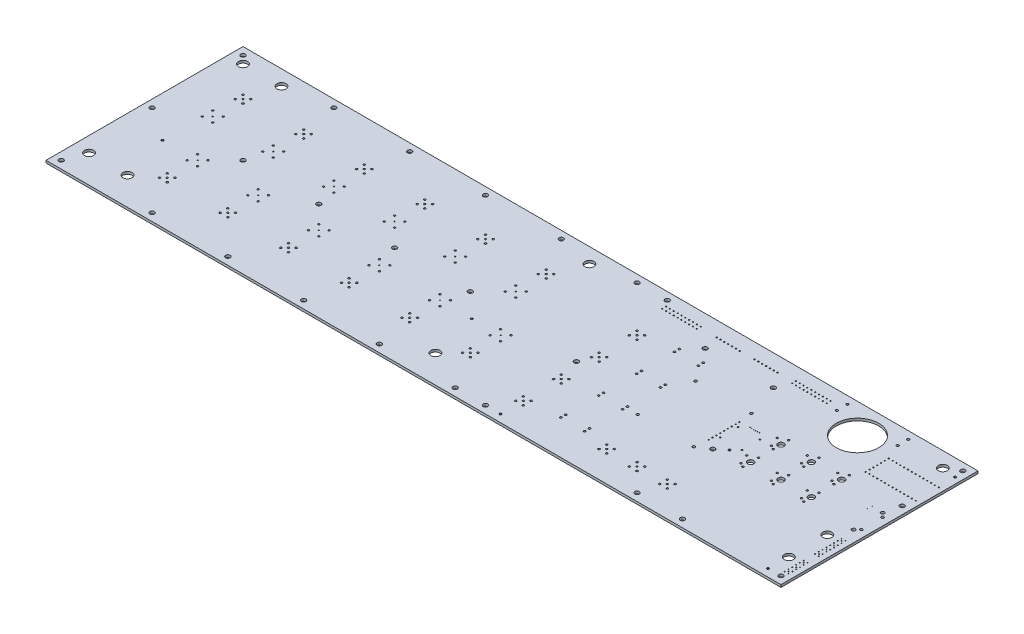
SolidWorks part; units mm, degrees
ref_plane "Front Plane" through (0, 0, 0) normal (0, 0, 1) x (1, 0, 0)
ref_plane "Top Plane" through (0, 0, 0) normal (0, 1, 0) x (1, 0, 0)
ref_plane "Right Plane" through (0, 0, 0) normal (1, 0, 0) x (0, 0, -1)
sketch "Sketch3" plane through (0, 0, 0) normal (0, 1, 0) x (1, 0, 0)
  line L0 (305, -60) -> (305, 70)
  line L1 (305, 70) -> (-180, 70)
  line L2 (-180, 70) -> (-180, -60)
  line L3 (-180, -60) -> (305, -60)
  line L4 (294.2, 12.3) -> (294.9, 12.3)
  line L5 (294.9, 12.3) -> (296.9, 10.3)
  line L6 (296.9, 10.3) -> (296.9, 7.3)
  line L7 (296.9, 7.3) -> (294.8, 5.2)
  line L8 (289.5428, 6.846) -> (290.4572, 6.846)
  line L9 (290.4572, 7.354) -> (289.5428, 7.354)
  line L10 (288.1572, 7.354) -> (287.2428, 7.354)
  line L11 (287.2428, 6.846) -> (288.1572, 6.846)
  line L12 (284.7428, 11.446) -> (285.6572, 11.446)
  line L13 (285.6572, 11.954) -> (284.7428, 11.954)
  line L14 (283.3572, 11.954) -> (282.4428, 11.954)
  line L15 (282.4428, 11.446) -> (283.3572, 11.446)
  line L16 (142.1275, 59.8291) -> (142.1275, 60.1709)
  line L17 (142.1275, 60.1709) -> (142.3691, 60.4125)
  line L18 (142.3691, 60.4125) -> (142.7109, 60.4125)
  line L19 (142.7109, 60.4125) -> (142.9525, 60.1709)
  line L20 (142.9525, 60.1709) -> (142.9525, 59.8291)
  line L21 (142.9525, 59.8291) -> (142.7109, 59.5875)
  line L22 (142.7109, 59.5875) -> (142.3691, 59.5875)
  line L23 (142.3691, 59.5875) -> (142.1275, 59.8291)
  line L24 (142.1275, 59.8291) -> (142.1275, 60.1709)
  line L25 (142.1275, 59.8291) -> (142.1275, 60.1709)
  line L26 (142.1275, 60.1709) -> (142.3691, 60.4125)
  line L27 (142.3691, 60.4125) -> (142.7109, 60.4125)
  line L28 (142.7109, 60.4125) -> (142.9525, 60.1709)
  line L29 (142.9525, 60.1709) -> (142.9525, 59.8291)
  line L30 (142.9525, 59.8291) -> (142.7109, 59.5875)
  line L31 (142.7109, 59.5875) -> (142.3691, 59.5875)
  line L32 (142.3691, 59.5875) -> (142.1275, 59.8291)
  line L33 (142.1275, 59.8291) -> (142.1275, 60.1709)
  line L34 (144.6675, 59.8291) -> (144.6675, 60.1709)
  line L35 (144.6675, 60.1709) -> (144.9091, 60.4125)
  line L36 (144.9091, 60.4125) -> (145.2509, 60.4125)
  line L37 (145.2509, 60.4125) -> (145.4925, 60.1709)
  line L38 (145.4925, 60.1709) -> (145.4925, 59.8291)
  line L39 (145.4925, 59.8291) -> (145.2509, 59.5875)
  line L40 (145.2509, 59.5875) -> (144.9091, 59.5875)
  line L41 (144.9091, 59.5875) -> (144.6675, 59.8291)
  line L42 (144.6675, 59.8291) -> (144.6675, 60.1709)
  line L43 (144.6675, 59.8291) -> (144.6675, 60.1709)
  line L44 (144.6675, 60.1709) -> (144.9091, 60.4125)
  line L45 (144.9091, 60.4125) -> (145.2509, 60.4125)
  line L46 (145.2509, 60.4125) -> (145.4925, 60.1709)
  line L47 (145.4925, 60.1709) -> (145.4925, 59.8291)
  line L48 (145.4925, 59.8291) -> (145.2509, 59.5875)
  line L49 (145.2509, 59.5875) -> (144.9091, 59.5875)
  line L50 (144.9091, 59.5875) -> (144.6675, 59.8291)
  line L51 (144.6675, 59.8291) -> (144.6675, 60.1709)
  line L52 (147.2075, 59.8291) -> (147.2075, 60.1709)
  line L53 (147.2075, 60.1709) -> (147.4491, 60.4125)
  line L54 (147.4491, 60.4125) -> (147.7909, 60.4125)
  line L55 (147.7909, 60.4125) -> (148.0325, 60.1709)
  line L56 (148.0325, 60.1709) -> (148.0325, 59.8291)
  line L57 (148.0325, 59.8291) -> (147.7909, 59.5875)
  line L58 (147.7909, 59.5875) -> (147.4491, 59.5875)
  line L59 (147.4491, 59.5875) -> (147.2075, 59.8291)
  line L60 (147.2075, 59.8291) -> (147.2075, 60.1709)
  line L61 (147.2075, 59.8291) -> (147.2075, 60.1709)
  line L62 (147.2075, 60.1709) -> (147.4491, 60.4125)
  line L63 (147.4491, 60.4125) -> (147.7909, 60.4125)
  line L64 (147.7909, 60.4125) -> (148.0325, 60.1709)
  line L65 (148.0325, 60.1709) -> (148.0325, 59.8291)
  line L66 (148.0325, 59.8291) -> (147.7909, 59.5875)
  line L67 (147.7909, 59.5875) -> (147.4491, 59.5875)
  line L68 (147.4491, 59.5875) -> (147.2075, 59.8291)
  line L69 (147.2075, 59.8291) -> (147.2075, 60.1709)
  line L70 (149.7475, 59.8291) -> (149.7475, 60.1709)
  line L71 (149.7475, 60.1709) -> (149.9891, 60.4125)
  line L72 (149.9891, 60.4125) -> (150.3309, 60.4125)
  line L73 (150.3309, 60.4125) -> (150.5725, 60.1709)
  line L74 (150.5725, 60.1709) -> (150.5725, 59.8291)
  line L75 (150.5725, 59.8291) -> (150.3309, 59.5875)
  line L76 (150.3309, 59.5875) -> (149.9891, 59.5875)
  line L77 (149.9891, 59.5875) -> (149.7475, 59.8291)
  line L78 (149.7475, 59.8291) -> (149.7475, 60.1709)
  line L79 (149.7475, 59.8291) -> (149.7475, 60.1709)
  line L80 (149.7475, 60.1709) -> (149.9891, 60.4125)
  line L81 (149.9891, 60.4125) -> (150.3309, 60.4125)
  line L82 (150.3309, 60.4125) -> (150.5725, 60.1709)
  line L83 (150.5725, 60.1709) -> (150.5725, 59.8291)
  line L84 (150.5725, 59.8291) -> (150.3309, 59.5875)
  line L85 (150.3309, 59.5875) -> (149.9891, 59.5875)
  line L86 (149.9891, 59.5875) -> (149.7475, 59.8291)
  line L87 (149.7475, 59.8291) -> (149.7475, 60.1709)
  line L88 (152.2875, 59.8291) -> (152.2875, 60.1709)
  line L89 (152.2875, 60.1709) -> (152.5291, 60.4125)
  line L90 (152.5291, 60.4125) -> (152.8709, 60.4125)
  line L91 (152.8709, 60.4125) -> (153.1125, 60.1709)
  line L92 (153.1125, 60.1709) -> (153.1125, 59.8291)
  line L93 (153.1125, 59.8291) -> (152.8709, 59.5875)
  line L94 (152.8709, 59.5875) -> (152.5291, 59.5875)
  line L95 (152.5291, 59.5875) -> (152.2875, 59.8291)
  line L96 (152.2875, 59.8291) -> (152.2875, 60.1709)
  line L97 (152.2875, 59.8291) -> (152.2875, 60.1709)
  line L98 (152.2875, 60.1709) -> (152.5291, 60.4125)
  line L99 (152.5291, 60.4125) -> (152.8709, 60.4125)
  line L100 (152.8709, 60.4125) -> (153.1125, 60.1709)
  line L101 (153.1125, 60.1709) -> (153.1125, 59.8291)
  line L102 (153.1125, 59.8291) -> (152.8709, 59.5875)
  line L103 (152.8709, 59.5875) -> (152.5291, 59.5875)
  line L104 (152.5291, 59.5875) -> (152.2875, 59.8291)
  line L105 (152.2875, 59.8291) -> (152.2875, 60.1709)
  line L106 (154.8275, 59.8291) -> (154.8275, 60.1709)
  line L107 (154.8275, 60.1709) -> (155.0691, 60.4125)
  line L108 (155.0691, 60.4125) -> (155.4109, 60.4125)
  line L109 (155.4109, 60.4125) -> (155.6525, 60.1709)
  line L110 (155.6525, 60.1709) -> (155.6525, 59.8291)
  line L111 (155.6525, 59.8291) -> (155.4109, 59.5875)
  line L112 (155.4109, 59.5875) -> (155.0691, 59.5875)
  line L113 (155.0691, 59.5875) -> (154.8275, 59.8291)
  line L114 (154.8275, 59.8291) -> (154.8275, 60.1709)
  line L115 (154.8275, 59.8291) -> (154.8275, 60.1709)
  line L116 (154.8275, 60.1709) -> (155.0691, 60.4125)
  line L117 (155.0691, 60.4125) -> (155.4109, 60.4125)
  line L118 (155.4109, 60.4125) -> (155.6525, 60.1709)
  line L119 (155.6525, 60.1709) -> (155.6525, 59.8291)
  line L120 (155.6525, 59.8291) -> (155.4109, 59.5875)
  line L121 (155.4109, 59.5875) -> (155.0691, 59.5875)
  line L122 (155.0691, 59.5875) -> (154.8275, 59.8291)
  line L123 (154.8275, 59.8291) -> (154.8275, 60.1709)
  line L124 (157.3675, 59.8291) -> (157.3675, 60.1709)
  line L125 (157.3675, 60.1709) -> (157.6091, 60.4125)
  line L126 (157.6091, 60.4125) -> (157.9509, 60.4125)
  line L127 (157.9509, 60.4125) -> (158.1925, 60.1709)
  line L128 (158.1925, 60.1709) -> (158.1925, 59.8291)
  line L129 (158.1925, 59.8291) -> (157.9509, 59.5875)
  line L130 (157.9509, 59.5875) -> (157.6091, 59.5875)
  line L131 (157.6091, 59.5875) -> (157.3675, 59.8291)
  line L132 (157.3675, 59.8291) -> (157.3675, 60.1709)
  line L133 (157.3675, 59.8291) -> (157.3675, 60.1709)
  line L134 (157.3675, 60.1709) -> (157.6091, 60.4125)
  line L135 (157.6091, 60.4125) -> (157.9509, 60.4125)
  line L136 (157.9509, 60.4125) -> (158.1925, 60.1709)
  line L137 (158.1925, 60.1709) -> (158.1925, 59.8291)
  line L138 (158.1925, 59.8291) -> (157.9509, 59.5875)
  line L139 (157.9509, 59.5875) -> (157.6091, 59.5875)
  line L140 (157.6091, 59.5875) -> (157.3675, 59.8291)
  line L141 (157.3675, 59.8291) -> (157.3675, 60.1709)
  line L142 (167.1275, 59.8291) -> (167.1275, 60.1709)
  line L143 (167.1275, 60.1709) -> (167.3691, 60.4125)
  line L144 (167.3691, 60.4125) -> (167.7109, 60.4125)
  line L145 (167.7109, 60.4125) -> (167.9525, 60.1709)
  line L146 (167.9525, 60.1709) -> (167.9525, 59.8291)
  line L147 (167.9525, 59.8291) -> (167.7109, 59.5875)
  line L148 (167.7109, 59.5875) -> (167.3691, 59.5875)
  line L149 (167.3691, 59.5875) -> (167.1275, 59.8291)
  line L150 (167.1275, 59.8291) -> (167.1275, 60.1709)
  line L151 (167.1275, 59.8291) -> (167.1275, 60.1709)
  line L152 (167.1275, 60.1709) -> (167.3691, 60.4125)
  line L153 (167.3691, 60.4125) -> (167.7109, 60.4125)
  line L154 (167.7109, 60.4125) -> (167.9525, 60.1709)
  line L155 (167.9525, 60.1709) -> (167.9525, 59.8291)
  line L156 (167.9525, 59.8291) -> (167.7109, 59.5875)
  line L157 (167.7109, 59.5875) -> (167.3691, 59.5875)
  line L158 (167.3691, 59.5875) -> (167.1275, 59.8291)
  line L159 (167.1275, 59.8291) -> (167.1275, 60.1709)
  line L160 (169.6675, 59.8291) -> (169.6675, 60.1709)
  line L161 (169.6675, 60.1709) -> (169.9091, 60.4125)
  line L162 (169.9091, 60.4125) -> (170.2509, 60.4125)
  line L163 (170.2509, 60.4125) -> (170.4925, 60.1709)
  line L164 (170.4925, 60.1709) -> (170.4925, 59.8291)
  line L165 (170.4925, 59.8291) -> (170.2509, 59.5875)
  line L166 (170.2509, 59.5875) -> (169.9091, 59.5875)
  line L167 (169.9091, 59.5875) -> (169.6675, 59.8291)
  line L168 (169.6675, 59.8291) -> (169.6675, 60.1709)
  line L169 (169.6675, 59.8291) -> (169.6675, 60.1709)
  line L170 (169.6675, 60.1709) -> (169.9091, 60.4125)
  line L171 (169.9091, 60.4125) -> (170.2509, 60.4125)
  line L172 (170.2509, 60.4125) -> (170.4925, 60.1709)
  line L173 (170.4925, 60.1709) -> (170.4925, 59.8291)
  line L174 (170.4925, 59.8291) -> (170.2509, 59.5875)
  line L175 (170.2509, 59.5875) -> (169.9091, 59.5875)
  line L176 (169.9091, 59.5875) -> (169.6675, 59.8291)
  line L177 (169.6675, 59.8291) -> (169.6675, 60.1709)
  line L178 (172.2075, 59.8291) -> (172.2075, 60.1709)
  line L179 (172.2075, 60.1709) -> (172.4491, 60.4125)
  line L180 (172.4491, 60.4125) -> (172.7909, 60.4125)
  line L181 (172.7909, 60.4125) -> (173.0325, 60.1709)
  line L182 (173.0325, 60.1709) -> (173.0325, 59.8291)
  line L183 (173.0325, 59.8291) -> (172.7909, 59.5875)
  line L184 (172.7909, 59.5875) -> (172.4491, 59.5875)
  line L185 (172.4491, 59.5875) -> (172.2075, 59.8291)
  line L186 (172.2075, 59.8291) -> (172.2075, 60.1709)
  line L187 (172.2075, 59.8291) -> (172.2075, 60.1709)
  line L188 (172.2075, 60.1709) -> (172.4491, 60.4125)
  line L189 (172.4491, 60.4125) -> (172.7909, 60.4125)
  line L190 (172.7909, 60.4125) -> (173.0325, 60.1709)
  line L191 (173.0325, 60.1709) -> (173.0325, 59.8291)
  line L192 (173.0325, 59.8291) -> (172.7909, 59.5875)
  line L193 (172.7909, 59.5875) -> (172.4491, 59.5875)
  line L194 (172.4491, 59.5875) -> (172.2075, 59.8291)
  line L195 (172.2075, 59.8291) -> (172.2075, 60.1709)
  line L196 (174.7475, 59.8291) -> (174.7475, 60.1709)
  line L197 (174.7475, 60.1709) -> (174.9891, 60.4125)
  line L198 (174.9891, 60.4125) -> (175.3309, 60.4125)
  line L199 (175.3309, 60.4125) -> (175.5725, 60.1709)
  line L200 (175.5725, 60.1709) -> (175.5725, 59.8291)
  line L201 (175.5725, 59.8291) -> (175.3309, 59.5875)
  line L202 (175.3309, 59.5875) -> (174.9891, 59.5875)
  line L203 (174.9891, 59.5875) -> (174.7475, 59.8291)
  line L204 (174.7475, 59.8291) -> (174.7475, 60.1709)
  line L205 (174.7475, 59.8291) -> (174.7475, 60.1709)
  line L206 (174.7475, 60.1709) -> (174.9891, 60.4125)
  line L207 (174.9891, 60.4125) -> (175.3309, 60.4125)
  line L208 (175.3309, 60.4125) -> (175.5725, 60.1709)
  line L209 (175.5725, 60.1709) -> (175.5725, 59.8291)
  line L210 (175.5725, 59.8291) -> (175.3309, 59.5875)
  line L211 (175.3309, 59.5875) -> (174.9891, 59.5875)
  line L212 (174.9891, 59.5875) -> (174.7475, 59.8291)
  line L213 (174.7475, 59.8291) -> (174.7475, 60.1709)
  line L214 (177.2875, 59.8291) -> (177.2875, 60.1709)
  line L215 (177.2875, 60.1709) -> (177.5291, 60.4125)
  line L216 (177.5291, 60.4125) -> (177.8709, 60.4125)
  line L217 (177.8709, 60.4125) -> (178.1125, 60.1709)
  line L218 (178.1125, 60.1709) -> (178.1125, 59.8291)
  line L219 (178.1125, 59.8291) -> (177.8709, 59.5875)
  line L220 (177.8709, 59.5875) -> (177.5291, 59.5875)
  line L221 (177.5291, 59.5875) -> (177.2875, 59.8291)
  line L222 (177.2875, 59.8291) -> (177.2875, 60.1709)
  line L223 (177.2875, 59.8291) -> (177.2875, 60.1709)
  line L224 (177.2875, 60.1709) -> (177.5291, 60.4125)
  line L225 (177.5291, 60.4125) -> (177.8709, 60.4125)
  line L226 (177.8709, 60.4125) -> (178.1125, 60.1709)
  line L227 (178.1125, 60.1709) -> (178.1125, 59.8291)
  line L228 (178.1125, 59.8291) -> (177.8709, 59.5875)
  line L229 (177.8709, 59.5875) -> (177.5291, 59.5875)
  line L230 (177.5291, 59.5875) -> (177.2875, 59.8291)
  line L231 (177.2875, 59.8291) -> (177.2875, 60.1709)
  line L232 (179.8275, 59.8291) -> (179.8275, 60.1709)
  line L233 (179.8275, 60.1709) -> (180.0691, 60.4125)
  line L234 (180.0691, 60.4125) -> (180.4109, 60.4125)
  line L235 (180.4109, 60.4125) -> (180.6525, 60.1709)
  line L236 (180.6525, 60.1709) -> (180.6525, 59.8291)
  line L237 (180.6525, 59.8291) -> (180.4109, 59.5875)
  line L238 (180.4109, 59.5875) -> (180.0691, 59.5875)
  line L239 (180.0691, 59.5875) -> (179.8275, 59.8291)
  line L240 (179.8275, 59.8291) -> (179.8275, 60.1709)
  line L241 (179.8275, 59.8291) -> (179.8275, 60.1709)
  line L242 (179.8275, 60.1709) -> (180.0691, 60.4125)
  line L243 (180.0691, 60.4125) -> (180.4109, 60.4125)
  line L244 (180.4109, 60.4125) -> (180.6525, 60.1709)
  line L245 (180.6525, 60.1709) -> (180.6525, 59.8291)
  line L246 (180.6525, 59.8291) -> (180.4109, 59.5875)
  line L247 (180.4109, 59.5875) -> (180.0691, 59.5875)
  line L248 (180.0691, 59.5875) -> (179.8275, 59.8291)
  line L249 (179.8275, 59.8291) -> (179.8275, 60.1709)
  line L250 (182.3675, 59.8291) -> (182.3675, 60.1709)
  line L251 (182.3675, 60.1709) -> (182.6091, 60.4125)
  line L252 (182.6091, 60.4125) -> (182.9509, 60.4125)
  line L253 (182.9509, 60.4125) -> (183.1925, 60.1709)
  line L254 (183.1925, 60.1709) -> (183.1925, 59.8291)
  line L255 (183.1925, 59.8291) -> (182.9509, 59.5875)
  line L256 (182.9509, 59.5875) -> (182.6091, 59.5875)
  line L257 (182.6091, 59.5875) -> (182.3675, 59.8291)
  line L258 (182.3675, 59.8291) -> (182.3675, 60.1709)
  line L259 (182.3675, 59.8291) -> (182.3675, 60.1709)
  line L260 (182.3675, 60.1709) -> (182.6091, 60.4125)
  line L261 (182.6091, 60.4125) -> (182.9509, 60.4125)
  line L262 (182.9509, 60.4125) -> (183.1925, 60.1709)
  line L263 (183.1925, 60.1709) -> (183.1925, 59.8291)
  line L264 (183.1925, 59.8291) -> (182.9509, 59.5875)
  line L265 (182.9509, 59.5875) -> (182.6091, 59.5875)
  line L266 (182.6091, 59.5875) -> (182.3675, 59.8291)
  line L267 (182.3675, 59.8291) -> (182.3675, 60.1709)
  line L268 (131.3929, 58.5621) -> (131.3929, 58.2779)
  line L269 (131.3929, 58.2779) -> (131.1921, 58.0771)
  line L270 (131.1921, 58.0771) -> (130.9079, 58.0771)
  line L271 (130.9079, 58.0771) -> (130.7071, 58.2779)
  line L272 (130.7071, 58.2779) -> (130.7071, 58.5621)
  line L273 (130.7071, 58.5621) -> (130.9079, 58.7629)
  line L274 (130.9079, 58.7629) -> (131.1921, 58.7629)
  line L275 (131.1921, 58.7629) -> (131.3929, 58.5621)
  line L276 (131.3929, 58.5621) -> (131.3929, 58.2779)
  line L277 (131.3929, 58.5621) -> (131.3929, 58.2779)
  line L278 (131.3929, 58.2779) -> (131.1921, 58.0771)
  line L279 (131.1921, 58.0771) -> (130.9079, 58.0771)
  line L280 (130.9079, 58.0771) -> (130.7071, 58.2779)
  line L281 (130.7071, 58.2779) -> (130.7071, 58.5621)
  line L282 (130.7071, 58.5621) -> (130.9079, 58.7629)
  line L283 (130.9079, 58.7629) -> (131.1921, 58.7629)
  line L284 (131.1921, 58.7629) -> (131.3929, 58.5621)
  line L285 (131.3929, 58.5621) -> (131.3929, 58.2779)
  line L286 (131.3929, 61.1021) -> (131.3929, 60.8179)
  line L287 (131.3929, 60.8179) -> (131.1921, 60.6171)
  line L288 (131.1921, 60.6171) -> (130.9079, 60.6171)
  line L289 (130.9079, 60.6171) -> (130.7071, 60.8179)
  line L290 (130.7071, 60.8179) -> (130.7071, 61.1021)
  line L291 (130.7071, 61.1021) -> (130.9079, 61.3029)
  line L292 (130.9079, 61.3029) -> (131.1921, 61.3029)
  line L293 (131.1921, 61.3029) -> (131.3929, 61.1021)
  line L294 (131.3929, 61.1021) -> (131.3929, 60.8179)
  line L295 (131.3929, 61.1021) -> (131.3929, 60.8179)
  line L296 (131.3929, 60.8179) -> (131.1921, 60.6171)
  line L297 (131.1921, 60.6171) -> (130.9079, 60.6171)
  line L298 (130.9079, 60.6171) -> (130.7071, 60.8179)
  line L299 (130.7071, 60.8179) -> (130.7071, 61.1021)
  line L300 (130.7071, 61.1021) -> (130.9079, 61.3029)
  line L301 (130.9079, 61.3029) -> (131.1921, 61.3029)
  line L302 (131.1921, 61.3029) -> (131.3929, 61.1021)
  line L303 (131.3929, 61.1021) -> (131.3929, 60.8179)
  line L304 (128.8529, 58.5621) -> (128.8529, 58.2779)
  line L305 (128.8529, 58.2779) -> (128.6521, 58.0771)
  line L306 (128.6521, 58.0771) -> (128.3679, 58.0771)
  line L307 (128.3679, 58.0771) -> (128.1671, 58.2779)
  line L308 (128.1671, 58.2779) -> (128.1671, 58.5621)
  line L309 (128.1671, 58.5621) -> (128.3679, 58.7629)
  line L310 (128.3679, 58.7629) -> (128.6521, 58.7629)
  line L311 (128.6521, 58.7629) -> (128.8529, 58.5621)
  line L312 (128.8529, 58.5621) -> (128.8529, 58.2779)
  line L313 (128.8529, 58.5621) -> (128.8529, 58.2779)
  line L314 (128.8529, 58.2779) -> (128.6521, 58.0771)
  line L315 (128.6521, 58.0771) -> (128.3679, 58.0771)
  line L316 (128.3679, 58.0771) -> (128.1671, 58.2779)
  line L317 (128.1671, 58.2779) -> (128.1671, 58.5621)
  line L318 (128.1671, 58.5621) -> (128.3679, 58.7629)
  line L319 (128.3679, 58.7629) -> (128.6521, 58.7629)
  line L320 (128.6521, 58.7629) -> (128.8529, 58.5621)
  line L321 (128.8529, 58.5621) -> (128.8529, 58.2779)
  line L322 (128.8529, 61.1021) -> (128.8529, 60.8179)
  line L323 (128.8529, 60.8179) -> (128.6521, 60.6171)
  line L324 (128.6521, 60.6171) -> (128.3679, 60.6171)
  line L325 (128.3679, 60.6171) -> (128.1671, 60.8179)
  line L326 (128.1671, 60.8179) -> (128.1671, 61.1021)
  line L327 (128.1671, 61.1021) -> (128.3679, 61.3029)
  line L328 (128.3679, 61.3029) -> (128.6521, 61.3029)
  line L329 (128.6521, 61.3029) -> (128.8529, 61.1021)
  line L330 (128.8529, 61.1021) -> (128.8529, 60.8179)
  line L331 (128.8529, 61.1021) -> (128.8529, 60.8179)
  line L332 (128.8529, 60.8179) -> (128.6521, 60.6171)
  line L333 (128.6521, 60.6171) -> (128.3679, 60.6171)
  line L334 (128.3679, 60.6171) -> (128.1671, 60.8179)
  line L335 (128.1671, 60.8179) -> (128.1671, 61.1021)
  line L336 (128.1671, 61.1021) -> (128.3679, 61.3029)
  line L337 (128.3679, 61.3029) -> (128.6521, 61.3029)
  line L338 (128.6521, 61.3029) -> (128.8529, 61.1021)
  line L339 (128.8529, 61.1021) -> (128.8529, 60.8179)
  line L340 (126.3129, 58.5621) -> (126.3129, 58.2779)
  line L341 (126.3129, 58.2779) -> (126.1121, 58.0771)
  line L342 (126.1121, 58.0771) -> (125.8279, 58.0771)
  line L343 (125.8279, 58.0771) -> (125.6271, 58.2779)
  line L344 (125.6271, 58.2779) -> (125.6271, 58.5621)
  line L345 (125.6271, 58.5621) -> (125.8279, 58.7629)
  line L346 (125.8279, 58.7629) -> (126.1121, 58.7629)
  line L347 (126.1121, 58.7629) -> (126.3129, 58.5621)
  line L348 (126.3129, 58.5621) -> (126.3129, 58.2779)
  line L349 (126.3129, 58.5621) -> (126.3129, 58.2779)
  line L350 (126.3129, 58.2779) -> (126.1121, 58.0771)
  line L351 (126.1121, 58.0771) -> (125.8279, 58.0771)
  line L352 (125.8279, 58.0771) -> (125.6271, 58.2779)
  line L353 (125.6271, 58.2779) -> (125.6271, 58.5621)
  line L354 (125.6271, 58.5621) -> (125.8279, 58.7629)
  line L355 (125.8279, 58.7629) -> (126.1121, 58.7629)
  line L356 (126.1121, 58.7629) -> (126.3129, 58.5621)
  line L357 (126.3129, 58.5621) -> (126.3129, 58.2779)
  line L358 (126.3129, 61.1021) -> (126.3129, 60.8179)
  line L359 (126.3129, 60.8179) -> (126.1121, 60.6171)
  line L360 (126.1121, 60.6171) -> (125.8279, 60.6171)
  line L361 (125.8279, 60.6171) -> (125.6271, 60.8179)
  line L362 (125.6271, 60.8179) -> (125.6271, 61.1021)
  line L363 (125.6271, 61.1021) -> (125.8279, 61.3029)
  line L364 (125.8279, 61.3029) -> (126.1121, 61.3029)
  line L365 (126.1121, 61.3029) -> (126.3129, 61.1021)
  line L366 (126.3129, 61.1021) -> (126.3129, 60.8179)
  line L367 (126.3129, 61.1021) -> (126.3129, 60.8179)
  line L368 (126.3129, 60.8179) -> (126.1121, 60.6171)
  line L369 (126.1121, 60.6171) -> (125.8279, 60.6171)
  line L370 (125.8279, 60.6171) -> (125.6271, 60.8179)
  line L371 (125.6271, 60.8179) -> (125.6271, 61.1021)
  line L372 (125.6271, 61.1021) -> (125.8279, 61.3029)
  line L373 (125.8279, 61.3029) -> (126.1121, 61.3029)
  line L374 (126.1121, 61.3029) -> (126.3129, 61.1021)
  line L375 (126.3129, 61.1021) -> (126.3129, 60.8179)
  line L376 (123.7729, 58.5621) -> (123.7729, 58.2779)
  line L377 (123.7729, 58.2779) -> (123.5721, 58.0771)
  line L378 (123.5721, 58.0771) -> (123.2879, 58.0771)
  line L379 (123.2879, 58.0771) -> (123.0871, 58.2779)
  line L380 (123.0871, 58.2779) -> (123.0871, 58.5621)
  line L381 (123.0871, 58.5621) -> (123.2879, 58.7629)
  line L382 (123.2879, 58.7629) -> (123.5721, 58.7629)
  line L383 (123.5721, 58.7629) -> (123.7729, 58.5621)
  line L384 (123.7729, 58.5621) -> (123.7729, 58.2779)
  line L385 (123.7729, 58.5621) -> (123.7729, 58.2779)
  line L386 (123.7729, 58.2779) -> (123.5721, 58.0771)
  line L387 (123.5721, 58.0771) -> (123.2879, 58.0771)
  line L388 (123.2879, 58.0771) -> (123.0871, 58.2779)
  line L389 (123.0871, 58.2779) -> (123.0871, 58.5621)
  line L390 (123.0871, 58.5621) -> (123.2879, 58.7629)
  line L391 (123.2879, 58.7629) -> (123.5721, 58.7629)
  line L392 (123.5721, 58.7629) -> (123.7729, 58.5621)
  line L393 (123.7729, 58.5621) -> (123.7729, 58.2779)
  line L394 (123.7729, 61.1021) -> (123.7729, 60.8179)
  line L395 (123.7729, 60.8179) -> (123.5721, 60.6171)
  line L396 (123.5721, 60.6171) -> (123.2879, 60.6171)
  line L397 (123.2879, 60.6171) -> (123.0871, 60.8179)
  line L398 (123.0871, 60.8179) -> (123.0871, 61.1021)
  line L399 (123.0871, 61.1021) -> (123.2879, 61.3029)
  line L400 (123.2879, 61.3029) -> (123.5721, 61.3029)
  line L401 (123.5721, 61.3029) -> (123.7729, 61.1021)
  line L402 (123.7729, 61.1021) -> (123.7729, 60.8179)
  line L403 (123.7729, 61.1021) -> (123.7729, 60.8179)
  line L404 (123.7729, 60.8179) -> (123.5721, 60.6171)
  line L405 (123.5721, 60.6171) -> (123.2879, 60.6171)
  line L406 (123.2879, 60.6171) -> (123.0871, 60.8179)
  line L407 (123.0871, 60.8179) -> (123.0871, 61.1021)
  line L408 (123.0871, 61.1021) -> (123.2879, 61.3029)
  line L409 (123.2879, 61.3029) -> (123.5721, 61.3029)
  line L410 (123.5721, 61.3029) -> (123.7729, 61.1021)
  line L411 (123.7729, 61.1021) -> (123.7729, 60.8179)
  line L412 (121.2329, 58.5621) -> (121.2329, 58.2779)
  line L413 (121.2329, 58.2779) -> (121.0321, 58.0771)
  line L414 (121.0321, 58.0771) -> (120.7479, 58.0771)
  line L415 (120.7479, 58.0771) -> (120.5471, 58.2779)
  line L416 (120.5471, 58.2779) -> (120.5471, 58.5621)
  line L417 (120.5471, 58.5621) -> (120.7479, 58.7629)
  line L418 (120.7479, 58.7629) -> (121.0321, 58.7629)
  line L419 (121.0321, 58.7629) -> (121.2329, 58.5621)
  line L420 (121.2329, 58.5621) -> (121.2329, 58.2779)
  line L421 (121.2329, 58.5621) -> (121.2329, 58.2779)
  line L422 (121.2329, 58.2779) -> (121.0321, 58.0771)
  line L423 (121.0321, 58.0771) -> (120.7479, 58.0771)
  line L424 (120.7479, 58.0771) -> (120.5471, 58.2779)
  line L425 (120.5471, 58.2779) -> (120.5471, 58.5621)
  line L426 (120.5471, 58.5621) -> (120.7479, 58.7629)
  line L427 (120.7479, 58.7629) -> (121.0321, 58.7629)
  line L428 (121.0321, 58.7629) -> (121.2329, 58.5621)
  line L429 (121.2329, 58.5621) -> (121.2329, 58.2779)
  line L430 (121.2329, 61.1021) -> (121.2329, 60.8179)
  line L431 (121.2329, 60.8179) -> (121.0321, 60.6171)
  line L432 (121.0321, 60.6171) -> (120.7479, 60.6171)
  line L433 (120.7479, 60.6171) -> (120.5471, 60.8179)
  line L434 (120.5471, 60.8179) -> (120.5471, 61.1021)
  line L435 (120.5471, 61.1021) -> (120.7479, 61.3029)
  line L436 (120.7479, 61.3029) -> (121.0321, 61.3029)
  line L437 (121.0321, 61.3029) -> (121.2329, 61.1021)
  line L438 (121.2329, 61.1021) -> (121.2329, 60.8179)
  line L439 (121.2329, 61.1021) -> (121.2329, 60.8179)
  line L440 (121.2329, 60.8179) -> (121.0321, 60.6171)
  line L441 (121.0321, 60.6171) -> (120.7479, 60.6171)
  line L442 (120.7479, 60.6171) -> (120.5471, 60.8179)
  line L443 (120.5471, 60.8179) -> (120.5471, 61.1021)
  line L444 (120.5471, 61.1021) -> (120.7479, 61.3029)
  line L445 (120.7479, 61.3029) -> (121.0321, 61.3029)
  line L446 (121.0321, 61.3029) -> (121.2329, 61.1021)
  line L447 (121.2329, 61.1021) -> (121.2329, 60.8179)
  line L448 (118.6929, 58.5621) -> (118.6929, 58.2779)
  line L449 (118.6929, 58.2779) -> (118.4921, 58.0771)
  line L450 (118.4921, 58.0771) -> (118.2079, 58.0771)
  line L451 (118.2079, 58.0771) -> (118.0071, 58.2779)
  line L452 (118.0071, 58.2779) -> (118.0071, 58.5621)
  line L453 (118.0071, 58.5621) -> (118.2079, 58.7629)
  line L454 (118.2079, 58.7629) -> (118.4921, 58.7629)
  line L455 (118.4921, 58.7629) -> (118.6929, 58.5621)
  line L456 (118.6929, 58.5621) -> (118.6929, 58.2779)
  line L457 (118.6929, 58.5621) -> (118.6929, 58.2779)
  line L458 (118.6929, 58.2779) -> (118.4921, 58.0771)
  line L459 (118.4921, 58.0771) -> (118.2079, 58.0771)
  line L460 (118.2079, 58.0771) -> (118.0071, 58.2779)
  line L461 (118.0071, 58.2779) -> (118.0071, 58.5621)
  line L462 (118.0071, 58.5621) -> (118.2079, 58.7629)
  line L463 (118.2079, 58.7629) -> (118.4921, 58.7629)
  line L464 (118.4921, 58.7629) -> (118.6929, 58.5621)
  line L465 (118.6929, 58.5621) -> (118.6929, 58.2779)
  line L466 (118.6929, 61.1021) -> (118.6929, 60.8179)
  line L467 (118.6929, 60.8179) -> (118.4921, 60.6171)
  line L468 (118.4921, 60.6171) -> (118.2079, 60.6171)
  line L469 (118.2079, 60.6171) -> (118.0071, 60.8179)
  line L470 (118.0071, 60.8179) -> (118.0071, 61.1021)
  line L471 (118.0071, 61.1021) -> (118.2079, 61.3029)
  line L472 (118.2079, 61.3029) -> (118.4921, 61.3029)
  line L473 (118.4921, 61.3029) -> (118.6929, 61.1021)
  line L474 (118.6929, 61.1021) -> (118.6929, 60.8179)
  line L475 (118.6929, 61.1021) -> (118.6929, 60.8179)
  line L476 (118.6929, 60.8179) -> (118.4921, 60.6171)
  line L477 (118.4921, 60.6171) -> (118.2079, 60.6171)
  line L478 (118.2079, 60.6171) -> (118.0071, 60.8179)
  line L479 (118.0071, 60.8179) -> (118.0071, 61.1021)
  line L480 (118.0071, 61.1021) -> (118.2079, 61.3029)
  line L481 (118.2079, 61.3029) -> (118.4921, 61.3029)
  line L482 (118.4921, 61.3029) -> (118.6929, 61.1021)
  line L483 (118.6929, 61.1021) -> (118.6929, 60.8179)
  line L484 (116.1529, 58.5621) -> (116.1529, 58.2779)
  line L485 (116.1529, 58.2779) -> (115.9521, 58.0771)
  line L486 (115.9521, 58.0771) -> (115.6679, 58.0771)
  line L487 (115.6679, 58.0771) -> (115.4671, 58.2779)
  line L488 (115.4671, 58.2779) -> (115.4671, 58.5621)
  line L489 (115.4671, 58.5621) -> (115.6679, 58.7629)
  line L490 (115.6679, 58.7629) -> (115.9521, 58.7629)
  line L491 (115.9521, 58.7629) -> (116.1529, 58.5621)
  line L492 (116.1529, 58.5621) -> (116.1529, 58.2779)
  line L493 (116.1529, 58.5621) -> (116.1529, 58.2779)
  line L494 (116.1529, 58.2779) -> (115.9521, 58.0771)
  line L495 (115.9521, 58.0771) -> (115.6679, 58.0771)
  line L496 (115.6679, 58.0771) -> (115.4671, 58.2779)
  line L497 (115.4671, 58.2779) -> (115.4671, 58.5621)
  line L498 (115.4671, 58.5621) -> (115.6679, 58.7629)
  line L499 (115.6679, 58.7629) -> (115.9521, 58.7629)
  line L500 (115.9521, 58.7629) -> (116.1529, 58.5621)
  line L501 (116.1529, 58.5621) -> (116.1529, 58.2779)
  line L502 (116.1529, 61.1021) -> (116.1529, 60.8179)
  line L503 (116.1529, 60.8179) -> (115.9521, 60.6171)
  line L504 (115.9521, 60.6171) -> (115.6679, 60.6171)
  line L505 (115.6679, 60.6171) -> (115.4671, 60.8179)
  line L506 (115.4671, 60.8179) -> (115.4671, 61.1021)
  line L507 (115.4671, 61.1021) -> (115.6679, 61.3029)
  line L508 (115.6679, 61.3029) -> (115.9521, 61.3029)
  line L509 (115.9521, 61.3029) -> (116.1529, 61.1021)
  line L510 (116.1529, 61.1021) -> (116.1529, 60.8179)
  line L511 (116.1529, 61.1021) -> (116.1529, 60.8179)
  line L512 (116.1529, 60.8179) -> (115.9521, 60.6171)
  line L513 (115.9521, 60.6171) -> (115.6679, 60.6171)
  line L514 (115.6679, 60.6171) -> (115.4671, 60.8179)
  line L515 (115.4671, 60.8179) -> (115.4671, 61.1021)
  line L516 (115.4671, 61.1021) -> (115.6679, 61.3029)
  line L517 (115.6679, 61.3029) -> (115.9521, 61.3029)
  line L518 (115.9521, 61.3029) -> (116.1529, 61.1021)
  line L519 (116.1529, 61.1021) -> (116.1529, 60.8179)
  line L520 (113.6129, 58.5621) -> (113.6129, 58.2779)
  line L521 (113.6129, 58.2779) -> (113.4121, 58.0771)
  line L522 (113.4121, 58.0771) -> (113.1279, 58.0771)
  line L523 (113.1279, 58.0771) -> (112.9271, 58.2779)
  line L524 (112.9271, 58.2779) -> (112.9271, 58.5621)
  line L525 (112.9271, 58.5621) -> (113.1279, 58.7629)
  line L526 (113.1279, 58.7629) -> (113.4121, 58.7629)
  line L527 (113.4121, 58.7629) -> (113.6129, 58.5621)
  line L528 (113.6129, 58.5621) -> (113.6129, 58.2779)
  line L529 (113.6129, 58.5621) -> (113.6129, 58.2779)
  line L530 (113.6129, 58.2779) -> (113.4121, 58.0771)
  line L531 (113.4121, 58.0771) -> (113.1279, 58.0771)
  line L532 (113.1279, 58.0771) -> (112.9271, 58.2779)
  line L533 (112.9271, 58.2779) -> (112.9271, 58.5621)
  line L534 (112.9271, 58.5621) -> (113.1279, 58.7629)
  line L535 (113.1279, 58.7629) -> (113.4121, 58.7629)
  line L536 (113.4121, 58.7629) -> (113.6129, 58.5621)
  line L537 (113.6129, 58.5621) -> (113.6129, 58.2779)
  line L538 (113.6129, 61.1021) -> (113.6129, 60.8179)
  line L539 (113.6129, 60.8179) -> (113.4121, 60.6171)
  line L540 (113.4121, 60.6171) -> (113.1279, 60.6171)
  line L541 (113.1279, 60.6171) -> (112.9271, 60.8179)
  line L542 (112.9271, 60.8179) -> (112.9271, 61.1021)
  line L543 (112.9271, 61.1021) -> (113.1279, 61.3029)
  line L544 (113.1279, 61.3029) -> (113.4121, 61.3029)
  line L545 (113.4121, 61.3029) -> (113.6129, 61.1021)
  line L546 (113.6129, 61.1021) -> (113.6129, 60.8179)
  line L547 (113.6129, 61.1021) -> (113.6129, 60.8179)
  line L548 (113.6129, 60.8179) -> (113.4121, 60.6171)
  line L549 (113.4121, 60.6171) -> (113.1279, 60.6171)
  line L550 (113.1279, 60.6171) -> (112.9271, 60.8179)
  line L551 (112.9271, 60.8179) -> (112.9271, 61.1021)
  line L552 (112.9271, 61.1021) -> (113.1279, 61.3029)
  line L553 (113.1279, 61.3029) -> (113.4121, 61.3029)
  line L554 (113.4121, 61.3029) -> (113.6129, 61.1021)
  line L555 (113.6129, 61.1021) -> (113.6129, 60.8179)
  line L556 (111.0729, 58.5621) -> (111.0729, 58.2779)
  line L557 (111.0729, 58.2779) -> (110.8721, 58.0771)
  line L558 (110.8721, 58.0771) -> (110.5879, 58.0771)
  line L559 (110.5879, 58.0771) -> (110.3871, 58.2779)
  line L560 (110.3871, 58.2779) -> (110.3871, 58.5621)
  line L561 (110.3871, 58.5621) -> (110.5879, 58.7629)
  line L562 (110.5879, 58.7629) -> (110.8721, 58.7629)
  line L563 (110.8721, 58.7629) -> (111.0729, 58.5621)
  line L564 (111.0729, 58.5621) -> (111.0729, 58.2779)
  line L565 (111.0729, 58.5621) -> (111.0729, 58.2779)
  line L566 (111.0729, 58.2779) -> (110.8721, 58.0771)
  line L567 (110.8721, 58.0771) -> (110.5879, 58.0771)
  line L568 (110.5879, 58.0771) -> (110.3871, 58.2779)
  line L569 (110.3871, 58.2779) -> (110.3871, 58.5621)
  line L570 (110.3871, 58.5621) -> (110.5879, 58.7629)
  line L571 (110.5879, 58.7629) -> (110.8721, 58.7629)
  line L572 (110.8721, 58.7629) -> (111.0729, 58.5621)
  line L573 (111.0729, 58.5621) -> (111.0729, 58.2779)
  line L574 (111.0729, 61.1021) -> (111.0729, 60.8179)
  line L575 (111.0729, 60.8179) -> (110.8721, 60.6171)
  line L576 (110.8721, 60.6171) -> (110.5879, 60.6171)
  line L577 (110.5879, 60.6171) -> (110.3871, 60.8179)
  line L578 (110.3871, 60.8179) -> (110.3871, 61.1021)
  line L579 (110.3871, 61.1021) -> (110.5879, 61.3029)
  line L580 (110.5879, 61.3029) -> (110.8721, 61.3029)
  line L581 (110.8721, 61.3029) -> (111.0729, 61.1021)
  line L582 (111.0729, 61.1021) -> (111.0729, 60.8179)
  line L583 (111.0729, 61.1021) -> (111.0729, 60.8179)
  line L584 (111.0729, 60.8179) -> (110.8721, 60.6171)
  line L585 (110.8721, 60.6171) -> (110.5879, 60.6171)
  line L586 (110.5879, 60.6171) -> (110.3871, 60.8179)
  line L587 (110.3871, 60.8179) -> (110.3871, 61.1021)
  line L588 (110.3871, 61.1021) -> (110.5879, 61.3029)
  line L589 (110.5879, 61.3029) -> (110.8721, 61.3029)
  line L590 (110.8721, 61.3029) -> (111.0729, 61.1021)
  line L591 (111.0729, 61.1021) -> (111.0729, 60.8179)
  line L592 (108.5329, 58.5621) -> (108.5329, 58.2779)
  line L593 (108.5329, 58.2779) -> (108.3321, 58.0771)
  line L594 (108.3321, 58.0771) -> (108.0479, 58.0771)
  line L595 (108.0479, 58.0771) -> (107.8471, 58.2779)
  line L596 (107.8471, 58.2779) -> (107.8471, 58.5621)
  line L597 (107.8471, 58.5621) -> (108.0479, 58.7629)
  line L598 (108.0479, 58.7629) -> (108.3321, 58.7629)
  line L599 (108.3321, 58.7629) -> (108.5329, 58.5621)
  line L600 (108.5329, 58.5621) -> (108.5329, 58.2779)
  line L601 (108.5329, 58.5621) -> (108.5329, 58.2779)
  line L602 (108.5329, 58.2779) -> (108.3321, 58.0771)
  line L603 (108.3321, 58.0771) -> (108.0479, 58.0771)
  line L604 (108.0479, 58.0771) -> (107.8471, 58.2779)
  line L605 (107.8471, 58.2779) -> (107.8471, 58.5621)
  line L606 (107.8471, 58.5621) -> (108.0479, 58.7629)
  line L607 (108.0479, 58.7629) -> (108.3321, 58.7629)
  line L608 (108.3321, 58.7629) -> (108.5329, 58.5621)
  line L609 (108.5329, 58.5621) -> (108.5329, 58.2779)
  line L610 (108.5329, 61.1021) -> (108.5329, 60.8179)
  line L611 (108.5329, 60.8179) -> (108.3321, 60.6171)
  line L612 (108.3321, 60.6171) -> (108.0479, 60.6171)
  line L613 (108.0479, 60.6171) -> (107.8471, 60.8179)
  line L614 (107.8471, 60.8179) -> (107.8471, 61.1021)
  line L615 (107.8471, 61.1021) -> (108.0479, 61.3029)
  line L616 (108.0479, 61.3029) -> (108.3321, 61.3029)
  line L617 (108.3321, 61.3029) -> (108.5329, 61.1021)
  line L618 (108.5329, 61.1021) -> (108.5329, 60.8179)
  line L619 (108.5329, 61.1021) -> (108.5329, 60.8179)
  line L620 (108.5329, 60.8179) -> (108.3321, 60.6171)
  line L621 (108.3321, 60.6171) -> (108.0479, 60.6171)
  line L622 (108.0479, 60.6171) -> (107.8471, 60.8179)
  line L623 (107.8471, 60.8179) -> (107.8471, 61.1021)
  line L624 (107.8471, 61.1021) -> (108.0479, 61.3029)
  line L625 (108.0479, 61.3029) -> (108.3321, 61.3029)
  line L626 (108.3321, 61.3029) -> (108.5329, 61.1021)
  line L627 (108.5329, 61.1021) -> (108.5329, 60.8179)
  line L628 (193.2271, 61.1279) -> (193.2271, 61.4121)
  line L629 (193.2271, 61.4121) -> (193.4279, 61.6129)
  line L630 (193.4279, 61.6129) -> (193.7121, 61.6129)
  line L631 (193.7121, 61.6129) -> (193.9129, 61.4121)
  line L632 (193.9129, 61.4121) -> (193.9129, 61.1279)
  line L633 (193.9129, 61.1279) -> (193.7121, 60.9271)
  line L634 (193.7121, 60.9271) -> (193.4279, 60.9271)
  line L635 (193.4279, 60.9271) -> (193.2271, 61.1279)
  line L636 (193.2271, 61.1279) -> (193.2271, 61.4121)
  line L637 (193.2271, 61.1279) -> (193.2271, 61.4121)
  line L638 (193.2271, 61.4121) -> (193.4279, 61.6129)
  line L639 (193.4279, 61.6129) -> (193.7121, 61.6129)
  line L640 (193.7121, 61.6129) -> (193.9129, 61.4121)
  line L641 (193.9129, 61.4121) -> (193.9129, 61.1279)
  line L642 (193.9129, 61.1279) -> (193.7121, 60.9271)
  line L643 (193.7121, 60.9271) -> (193.4279, 60.9271)
  line L644 (193.4279, 60.9271) -> (193.2271, 61.1279)
  line L645 (193.2271, 61.1279) -> (193.2271, 61.4121)
  line L646 (193.2271, 58.5879) -> (193.2271, 58.8721)
  line L647 (193.2271, 58.8721) -> (193.4279, 59.0729)
  line L648 (193.4279, 59.0729) -> (193.7121, 59.0729)
  line L649 (193.7121, 59.0729) -> (193.9129, 58.8721)
  line L650 (193.9129, 58.8721) -> (193.9129, 58.5879)
  line L651 (193.9129, 58.5879) -> (193.7121, 58.3871)
  line L652 (193.7121, 58.3871) -> (193.4279, 58.3871)
  line L653 (193.4279, 58.3871) -> (193.2271, 58.5879)
  line L654 (193.2271, 58.5879) -> (193.2271, 58.8721)
  line L655 (193.2271, 58.5879) -> (193.2271, 58.8721)
  line L656 (193.2271, 58.8721) -> (193.4279, 59.0729)
  line L657 (193.4279, 59.0729) -> (193.7121, 59.0729)
  line L658 (193.7121, 59.0729) -> (193.9129, 58.8721)
  line L659 (193.9129, 58.8721) -> (193.9129, 58.5879)
  line L660 (193.9129, 58.5879) -> (193.7121, 58.3871)
  line L661 (193.7121, 58.3871) -> (193.4279, 58.3871)
  line L662 (193.4279, 58.3871) -> (193.2271, 58.5879)
  line L663 (193.2271, 58.5879) -> (193.2271, 58.8721)
  line L664 (195.7671, 61.1279) -> (195.7671, 61.4121)
  line L665 (195.7671, 61.4121) -> (195.9679, 61.6129)
  line L666 (195.9679, 61.6129) -> (196.2521, 61.6129)
  line L667 (196.2521, 61.6129) -> (196.4529, 61.4121)
  line L668 (196.4529, 61.4121) -> (196.4529, 61.1279)
  line L669 (196.4529, 61.1279) -> (196.2521, 60.9271)
  line L670 (196.2521, 60.9271) -> (195.9679, 60.9271)
  line L671 (195.9679, 60.9271) -> (195.7671, 61.1279)
  line L672 (195.7671, 61.1279) -> (195.7671, 61.4121)
  line L673 (195.7671, 61.1279) -> (195.7671, 61.4121)
  line L674 (195.7671, 61.4121) -> (195.9679, 61.6129)
  line L675 (195.9679, 61.6129) -> (196.2521, 61.6129)
  line L676 (196.2521, 61.6129) -> (196.4529, 61.4121)
  line L677 (196.4529, 61.4121) -> (196.4529, 61.1279)
  line L678 (196.4529, 61.1279) -> (196.2521, 60.9271)
  line L679 (196.2521, 60.9271) -> (195.9679, 60.9271)
  line L680 (195.9679, 60.9271) -> (195.7671, 61.1279)
  line L681 (195.7671, 61.1279) -> (195.7671, 61.4121)
  line L682 (195.7671, 58.5879) -> (195.7671, 58.8721)
  line L683 (195.7671, 58.8721) -> (195.9679, 59.0729)
  line L684 (195.9679, 59.0729) -> (196.2521, 59.0729)
  line L685 (196.2521, 59.0729) -> (196.4529, 58.8721)
  line L686 (196.4529, 58.8721) -> (196.4529, 58.5879)
  line L687 (196.4529, 58.5879) -> (196.2521, 58.3871)
  line L688 (196.2521, 58.3871) -> (195.9679, 58.3871)
  line L689 (195.9679, 58.3871) -> (195.7671, 58.5879)
  line L690 (195.7671, 58.5879) -> (195.7671, 58.8721)
  line L691 (195.7671, 58.5879) -> (195.7671, 58.8721)
  line L692 (195.7671, 58.8721) -> (195.9679, 59.0729)
  line L693 (195.9679, 59.0729) -> (196.2521, 59.0729)
  line L694 (196.2521, 59.0729) -> (196.4529, 58.8721)
  line L695 (196.4529, 58.8721) -> (196.4529, 58.5879)
  line L696 (196.4529, 58.5879) -> (196.2521, 58.3871)
  line L697 (196.2521, 58.3871) -> (195.9679, 58.3871)
  line L698 (195.9679, 58.3871) -> (195.7671, 58.5879)
  line L699 (195.7671, 58.5879) -> (195.7671, 58.8721)
  line L700 (198.3071, 61.1279) -> (198.3071, 61.4121)
  line L701 (198.3071, 61.4121) -> (198.5079, 61.6129)
  line L702 (198.5079, 61.6129) -> (198.7921, 61.6129)
  line L703 (198.7921, 61.6129) -> (198.9929, 61.4121)
  line L704 (198.9929, 61.4121) -> (198.9929, 61.1279)
  line L705 (198.9929, 61.1279) -> (198.7921, 60.9271)
  line L706 (198.7921, 60.9271) -> (198.5079, 60.9271)
  line L707 (198.5079, 60.9271) -> (198.3071, 61.1279)
  line L708 (198.3071, 61.1279) -> (198.3071, 61.4121)
  line L709 (198.3071, 61.1279) -> (198.3071, 61.4121)
  line L710 (198.3071, 61.4121) -> (198.5079, 61.6129)
  line L711 (198.5079, 61.6129) -> (198.7921, 61.6129)
  line L712 (198.7921, 61.6129) -> (198.9929, 61.4121)
  line L713 (198.9929, 61.4121) -> (198.9929, 61.1279)
  line L714 (198.9929, 61.1279) -> (198.7921, 60.9271)
  line L715 (198.7921, 60.9271) -> (198.5079, 60.9271)
  line L716 (198.5079, 60.9271) -> (198.3071, 61.1279)
  line L717 (198.3071, 61.1279) -> (198.3071, 61.4121)
  line L718 (198.3071, 58.5879) -> (198.3071, 58.8721)
  line L719 (198.3071, 58.8721) -> (198.5079, 59.0729)
  line L720 (198.5079, 59.0729) -> (198.7921, 59.0729)
  line L721 (198.7921, 59.0729) -> (198.9929, 58.8721)
  line L722 (198.9929, 58.8721) -> (198.9929, 58.5879)
  line L723 (198.9929, 58.5879) -> (198.7921, 58.3871)
  line L724 (198.7921, 58.3871) -> (198.5079, 58.3871)
  line L725 (198.5079, 58.3871) -> (198.3071, 58.5879)
  line L726 (198.3071, 58.5879) -> (198.3071, 58.8721)
  line L727 (198.3071, 58.5879) -> (198.3071, 58.8721)
  line L728 (198.3071, 58.8721) -> (198.5079, 59.0729)
  line L729 (198.5079, 59.0729) -> (198.7921, 59.0729)
  line L730 (198.7921, 59.0729) -> (198.9929, 58.8721)
  line L731 (198.9929, 58.8721) -> (198.9929, 58.5879)
  line L732 (198.9929, 58.5879) -> (198.7921, 58.3871)
  line L733 (198.7921, 58.3871) -> (198.5079, 58.3871)
  line L734 (198.5079, 58.3871) -> (198.3071, 58.5879)
  line L735 (198.3071, 58.5879) -> (198.3071, 58.8721)
  line L736 (200.8471, 61.1279) -> (200.8471, 61.4121)
  line L737 (200.8471, 61.4121) -> (201.0479, 61.6129)
  line L738 (201.0479, 61.6129) -> (201.3321, 61.6129)
  line L739 (201.3321, 61.6129) -> (201.5329, 61.4121)
  line L740 (201.5329, 61.4121) -> (201.5329, 61.1279)
  line L741 (201.5329, 61.1279) -> (201.3321, 60.9271)
  line L742 (201.3321, 60.9271) -> (201.0479, 60.9271)
  line L743 (201.0479, 60.9271) -> (200.8471, 61.1279)
  line L744 (200.8471, 61.1279) -> (200.8471, 61.4121)
  line L745 (200.8471, 61.1279) -> (200.8471, 61.4121)
  line L746 (200.8471, 61.4121) -> (201.0479, 61.6129)
  line L747 (201.0479, 61.6129) -> (201.3321, 61.6129)
  line L748 (201.3321, 61.6129) -> (201.5329, 61.4121)
  line L749 (201.5329, 61.4121) -> (201.5329, 61.1279)
  line L750 (201.5329, 61.1279) -> (201.3321, 60.9271)
  line L751 (201.3321, 60.9271) -> (201.0479, 60.9271)
  line L752 (201.0479, 60.9271) -> (200.8471, 61.1279)
  line L753 (200.8471, 61.1279) -> (200.8471, 61.4121)
  line L754 (200.8471, 58.5879) -> (200.8471, 58.8721)
  line L755 (200.8471, 58.8721) -> (201.0479, 59.0729)
  line L756 (201.0479, 59.0729) -> (201.3321, 59.0729)
  line L757 (201.3321, 59.0729) -> (201.5329, 58.8721)
  line L758 (201.5329, 58.8721) -> (201.5329, 58.5879)
  line L759 (201.5329, 58.5879) -> (201.3321, 58.3871)
  line L760 (201.3321, 58.3871) -> (201.0479, 58.3871)
  line L761 (201.0479, 58.3871) -> (200.8471, 58.5879)
  line L762 (200.8471, 58.5879) -> (200.8471, 58.8721)
  line L763 (200.8471, 58.5879) -> (200.8471, 58.8721)
  line L764 (200.8471, 58.8721) -> (201.0479, 59.0729)
  line L765 (201.0479, 59.0729) -> (201.3321, 59.0729)
  line L766 (201.3321, 59.0729) -> (201.5329, 58.8721)
  line L767 (201.5329, 58.8721) -> (201.5329, 58.5879)
  line L768 (201.5329, 58.5879) -> (201.3321, 58.3871)
  line L769 (201.3321, 58.3871) -> (201.0479, 58.3871)
  line L770 (201.0479, 58.3871) -> (200.8471, 58.5879)
  line L771 (200.8471, 58.5879) -> (200.8471, 58.8721)
  line L772 (203.3871, 61.1279) -> (203.3871, 61.4121)
  line L773 (203.3871, 61.4121) -> (203.5879, 61.6129)
  line L774 (203.5879, 61.6129) -> (203.8721, 61.6129)
  line L775 (203.8721, 61.6129) -> (204.0729, 61.4121)
  line L776 (204.0729, 61.4121) -> (204.0729, 61.1279)
  line L777 (204.0729, 61.1279) -> (203.8721, 60.9271)
  line L778 (203.8721, 60.9271) -> (203.5879, 60.9271)
  line L779 (203.5879, 60.9271) -> (203.3871, 61.1279)
  line L780 (203.3871, 61.1279) -> (203.3871, 61.4121)
  line L781 (203.3871, 61.1279) -> (203.3871, 61.4121)
  line L782 (203.3871, 61.4121) -> (203.5879, 61.6129)
  line L783 (203.5879, 61.6129) -> (203.8721, 61.6129)
  line L784 (203.8721, 61.6129) -> (204.0729, 61.4121)
  line L785 (204.0729, 61.4121) -> (204.0729, 61.1279)
  line L786 (204.0729, 61.1279) -> (203.8721, 60.9271)
  line L787 (203.8721, 60.9271) -> (203.5879, 60.9271)
  line L788 (203.5879, 60.9271) -> (203.3871, 61.1279)
  line L789 (203.3871, 61.1279) -> (203.3871, 61.4121)
  line L790 (203.3871, 58.5879) -> (203.3871, 58.8721)
  line L791 (203.3871, 58.8721) -> (203.5879, 59.0729)
  line L792 (203.5879, 59.0729) -> (203.8721, 59.0729)
  line L793 (203.8721, 59.0729) -> (204.0729, 58.8721)
  line L794 (204.0729, 58.8721) -> (204.0729, 58.5879)
  line L795 (204.0729, 58.5879) -> (203.8721, 58.3871)
  line L796 (203.8721, 58.3871) -> (203.5879, 58.3871)
  line L797 (203.5879, 58.3871) -> (203.3871, 58.5879)
  line L798 (203.3871, 58.5879) -> (203.3871, 58.8721)
  line L799 (203.3871, 58.5879) -> (203.3871, 58.8721)
  line L800 (203.3871, 58.8721) -> (203.5879, 59.0729)
  line L801 (203.5879, 59.0729) -> (203.8721, 59.0729)
  line L802 (203.8721, 59.0729) -> (204.0729, 58.8721)
  line L803 (204.0729, 58.8721) -> (204.0729, 58.5879)
  line L804 (204.0729, 58.5879) -> (203.8721, 58.3871)
  line L805 (203.8721, 58.3871) -> (203.5879, 58.3871)
  line L806 (203.5879, 58.3871) -> (203.3871, 58.5879)
  line L807 (203.3871, 58.5879) -> (203.3871, 58.8721)
  line L808 (205.9271, 61.1279) -> (205.9271, 61.4121)
  line L809 (205.9271, 61.4121) -> (206.1279, 61.6129)
  line L810 (206.1279, 61.6129) -> (206.4121, 61.6129)
  line L811 (206.4121, 61.6129) -> (206.6129, 61.4121)
  line L812 (206.6129, 61.4121) -> (206.6129, 61.1279)
  line L813 (206.6129, 61.1279) -> (206.4121, 60.9271)
  line L814 (206.4121, 60.9271) -> (206.1279, 60.9271)
  line L815 (206.1279, 60.9271) -> (205.9271, 61.1279)
  line L816 (205.9271, 61.1279) -> (205.9271, 61.4121)
  line L817 (205.9271, 61.1279) -> (205.9271, 61.4121)
  line L818 (205.9271, 61.4121) -> (206.1279, 61.6129)
  line L819 (206.1279, 61.6129) -> (206.4121, 61.6129)
  line L820 (206.4121, 61.6129) -> (206.6129, 61.4121)
  line L821 (206.6129, 61.4121) -> (206.6129, 61.1279)
  line L822 (206.6129, 61.1279) -> (206.4121, 60.9271)
  line L823 (206.4121, 60.9271) -> (206.1279, 60.9271)
  line L824 (206.1279, 60.9271) -> (205.9271, 61.1279)
  line L825 (205.9271, 61.1279) -> (205.9271, 61.4121)
  line L826 (205.9271, 58.5879) -> (205.9271, 58.8721)
  line L827 (205.9271, 58.8721) -> (206.1279, 59.0729)
  line L828 (206.1279, 59.0729) -> (206.4121, 59.0729)
  line L829 (206.4121, 59.0729) -> (206.6129, 58.8721)
  line L830 (206.6129, 58.8721) -> (206.6129, 58.5879)
  line L831 (206.6129, 58.5879) -> (206.4121, 58.3871)
  line L832 (206.4121, 58.3871) -> (206.1279, 58.3871)
  line L833 (206.1279, 58.3871) -> (205.9271, 58.5879)
  line L834 (205.9271, 58.5879) -> (205.9271, 58.8721)
  line L835 (205.9271, 58.5879) -> (205.9271, 58.8721)
  line L836 (205.9271, 58.8721) -> (206.1279, 59.0729)
  line L837 (206.1279, 59.0729) -> (206.4121, 59.0729)
  line L838 (206.4121, 59.0729) -> (206.6129, 58.8721)
  line L839 (206.6129, 58.8721) -> (206.6129, 58.5879)
  line L840 (206.6129, 58.5879) -> (206.4121, 58.3871)
  line L841 (206.4121, 58.3871) -> (206.1279, 58.3871)
  line L842 (206.1279, 58.3871) -> (205.9271, 58.5879)
  line L843 (205.9271, 58.5879) -> (205.9271, 58.8721)
  line L844 (208.4671, 61.1279) -> (208.4671, 61.4121)
  line L845 (208.4671, 61.4121) -> (208.6679, 61.6129)
  line L846 (208.6679, 61.6129) -> (208.9521, 61.6129)
  line L847 (208.9521, 61.6129) -> (209.1529, 61.4121)
  line L848 (209.1529, 61.4121) -> (209.1529, 61.1279)
  line L849 (209.1529, 61.1279) -> (208.9521, 60.9271)
  line L850 (208.9521, 60.9271) -> (208.6679, 60.9271)
  line L851 (208.6679, 60.9271) -> (208.4671, 61.1279)
  line L852 (208.4671, 61.1279) -> (208.4671, 61.4121)
  line L853 (208.4671, 61.1279) -> (208.4671, 61.4121)
  line L854 (208.4671, 61.4121) -> (208.6679, 61.6129)
  line L855 (208.6679, 61.6129) -> (208.9521, 61.6129)
  line L856 (208.9521, 61.6129) -> (209.1529, 61.4121)
  line L857 (209.1529, 61.4121) -> (209.1529, 61.1279)
  line L858 (209.1529, 61.1279) -> (208.9521, 60.9271)
  line L859 (208.9521, 60.9271) -> (208.6679, 60.9271)
  line L860 (208.6679, 60.9271) -> (208.4671, 61.1279)
  line L861 (208.4671, 61.1279) -> (208.4671, 61.4121)
  line L862 (208.4671, 58.5879) -> (208.4671, 58.8721)
  line L863 (208.4671, 58.8721) -> (208.6679, 59.0729)
  line L864 (208.6679, 59.0729) -> (208.9521, 59.0729)
  line L865 (208.9521, 59.0729) -> (209.1529, 58.8721)
  line L866 (209.1529, 58.8721) -> (209.1529, 58.5879)
  line L867 (209.1529, 58.5879) -> (208.9521, 58.3871)
  line L868 (208.9521, 58.3871) -> (208.6679, 58.3871)
  line L869 (208.6679, 58.3871) -> (208.4671, 58.5879)
  line L870 (208.4671, 58.5879) -> (208.4671, 58.8721)
  line L871 (208.4671, 58.5879) -> (208.4671, 58.8721)
  line L872 (208.4671, 58.8721) -> (208.6679, 59.0729)
  line L873 (208.6679, 59.0729) -> (208.9521, 59.0729)
  line L874 (208.9521, 59.0729) -> (209.1529, 58.8721)
  line L875 (209.1529, 58.8721) -> (209.1529, 58.5879)
  line L876 (209.1529, 58.5879) -> (208.9521, 58.3871)
  line L877 (208.9521, 58.3871) -> (208.6679, 58.3871)
  line L878 (208.6679, 58.3871) -> (208.4671, 58.5879)
  line L879 (208.4671, 58.5879) -> (208.4671, 58.8721)
  line L880 (211.0071, 61.1279) -> (211.0071, 61.4121)
  line L881 (211.0071, 61.4121) -> (211.2079, 61.6129)
  line L882 (211.2079, 61.6129) -> (211.4921, 61.6129)
  line L883 (211.4921, 61.6129) -> (211.6929, 61.4121)
  line L884 (211.6929, 61.4121) -> (211.6929, 61.1279)
  line L885 (211.6929, 61.1279) -> (211.4921, 60.9271)
  line L886 (211.4921, 60.9271) -> (211.2079, 60.9271)
  line L887 (211.2079, 60.9271) -> (211.0071, 61.1279)
  line L888 (211.0071, 61.1279) -> (211.0071, 61.4121)
  line L889 (211.0071, 61.1279) -> (211.0071, 61.4121)
  line L890 (211.0071, 61.4121) -> (211.2079, 61.6129)
  line L891 (211.2079, 61.6129) -> (211.4921, 61.6129)
  line L892 (211.4921, 61.6129) -> (211.6929, 61.4121)
  line L893 (211.6929, 61.4121) -> (211.6929, 61.1279)
  line L894 (211.6929, 61.1279) -> (211.4921, 60.9271)
  line L895 (211.4921, 60.9271) -> (211.2079, 60.9271)
  line L896 (211.2079, 60.9271) -> (211.0071, 61.1279)
  line L897 (211.0071, 61.1279) -> (211.0071, 61.4121)
  line L898 (211.0071, 58.5879) -> (211.0071, 58.8721)
  line L899 (211.0071, 58.8721) -> (211.2079, 59.0729)
  line L900 (211.2079, 59.0729) -> (211.4921, 59.0729)
  line L901 (211.4921, 59.0729) -> (211.6929, 58.8721)
  line L902 (211.6929, 58.8721) -> (211.6929, 58.5879)
  line L903 (211.6929, 58.5879) -> (211.4921, 58.3871)
  line L904 (211.4921, 58.3871) -> (211.2079, 58.3871)
  line L905 (211.2079, 58.3871) -> (211.0071, 58.5879)
  line L906 (211.0071, 58.5879) -> (211.0071, 58.8721)
  line L907 (211.0071, 58.5879) -> (211.0071, 58.8721)
  line L908 (211.0071, 58.8721) -> (211.2079, 59.0729)
  line L909 (211.2079, 59.0729) -> (211.4921, 59.0729)
  line L910 (211.4921, 59.0729) -> (211.6929, 58.8721)
  line L911 (211.6929, 58.8721) -> (211.6929, 58.5879)
  line L912 (211.6929, 58.5879) -> (211.4921, 58.3871)
  line L913 (211.4921, 58.3871) -> (211.2079, 58.3871)
  line L914 (211.2079, 58.3871) -> (211.0071, 58.5879)
  line L915 (211.0071, 58.5879) -> (211.0071, 58.8721)
  line L916 (213.5471, 61.1279) -> (213.5471, 61.4121)
  line L917 (213.5471, 61.4121) -> (213.7479, 61.6129)
  line L918 (213.7479, 61.6129) -> (214.0321, 61.6129)
  line L919 (214.0321, 61.6129) -> (214.2329, 61.4121)
  line L920 (214.2329, 61.4121) -> (214.2329, 61.1279)
  line L921 (214.2329, 61.1279) -> (214.0321, 60.9271)
  line L922 (214.0321, 60.9271) -> (213.7479, 60.9271)
  line L923 (213.7479, 60.9271) -> (213.5471, 61.1279)
  line L924 (213.5471, 61.1279) -> (213.5471, 61.4121)
  line L925 (213.5471, 61.1279) -> (213.5471, 61.4121)
  line L926 (213.5471, 61.4121) -> (213.7479, 61.6129)
  line L927 (213.7479, 61.6129) -> (214.0321, 61.6129)
  line L928 (214.0321, 61.6129) -> (214.2329, 61.4121)
  line L929 (214.2329, 61.4121) -> (214.2329, 61.1279)
  line L930 (214.2329, 61.1279) -> (214.0321, 60.9271)
  line L931 (214.0321, 60.9271) -> (213.7479, 60.9271)
  line L932 (213.7479, 60.9271) -> (213.5471, 61.1279)
  line L933 (213.5471, 61.1279) -> (213.5471, 61.4121)
  line L934 (213.5471, 58.5879) -> (213.5471, 58.8721)
  line L935 (213.5471, 58.8721) -> (213.7479, 59.0729)
  line L936 (213.7479, 59.0729) -> (214.0321, 59.0729)
  line L937 (214.0321, 59.0729) -> (214.2329, 58.8721)
  line L938 (214.2329, 58.8721) -> (214.2329, 58.5879)
  line L939 (214.2329, 58.5879) -> (214.0321, 58.3871)
  line L940 (214.0321, 58.3871) -> (213.7479, 58.3871)
  line L941 (213.7479, 58.3871) -> (213.5471, 58.5879)
  line L942 (213.5471, 58.5879) -> (213.5471, 58.8721)
  line L943 (213.5471, 58.5879) -> (213.5471, 58.8721)
  line L944 (213.5471, 58.8721) -> (213.7479, 59.0729)
  line L945 (213.7479, 59.0729) -> (214.0321, 59.0729)
  line L946 (214.0321, 59.0729) -> (214.2329, 58.8721)
  line L947 (214.2329, 58.8721) -> (214.2329, 58.5879)
  line L948 (214.2329, 58.5879) -> (214.0321, 58.3871)
  line L949 (214.0321, 58.3871) -> (213.7479, 58.3871)
  line L950 (213.7479, 58.3871) -> (213.5471, 58.5879)
  line L951 (213.5471, 58.5879) -> (213.5471, 58.8721)
  line L952 (216.0871, 61.1279) -> (216.0871, 61.4121)
  line L953 (216.0871, 61.4121) -> (216.2879, 61.6129)
  line L954 (216.2879, 61.6129) -> (216.5721, 61.6129)
  line L955 (216.5721, 61.6129) -> (216.7729, 61.4121)
  line L956 (216.7729, 61.4121) -> (216.7729, 61.1279)
  line L957 (216.7729, 61.1279) -> (216.5721, 60.9271)
  line L958 (216.5721, 60.9271) -> (216.2879, 60.9271)
  line L959 (216.2879, 60.9271) -> (216.0871, 61.1279)
  line L960 (216.0871, 61.1279) -> (216.0871, 61.4121)
  line L961 (216.0871, 61.1279) -> (216.0871, 61.4121)
  line L962 (216.0871, 61.4121) -> (216.2879, 61.6129)
  line L963 (216.2879, 61.6129) -> (216.5721, 61.6129)
  line L964 (216.5721, 61.6129) -> (216.7729, 61.4121)
  line L965 (216.7729, 61.4121) -> (216.7729, 61.1279)
  line L966 (216.7729, 61.1279) -> (216.5721, 60.9271)
  line L967 (216.5721, 60.9271) -> (216.2879, 60.9271)
  line L968 (216.2879, 60.9271) -> (216.0871, 61.1279)
  line L969 (216.0871, 61.1279) -> (216.0871, 61.4121)
  line L970 (216.0871, 58.5879) -> (216.0871, 58.8721)
  line L971 (216.0871, 58.8721) -> (216.2879, 59.0729)
  line L972 (216.2879, 59.0729) -> (216.5721, 59.0729)
  line L973 (216.5721, 59.0729) -> (216.7729, 58.8721)
  line L974 (216.7729, 58.8721) -> (216.7729, 58.5879)
  line L975 (216.7729, 58.5879) -> (216.5721, 58.3871)
  line L976 (216.5721, 58.3871) -> (216.2879, 58.3871)
  line L977 (216.2879, 58.3871) -> (216.0871, 58.5879)
  line L978 (216.0871, 58.5879) -> (216.0871, 58.8721)
  line L979 (216.0871, 58.5879) -> (216.0871, 58.8721)
  line L980 (216.0871, 58.8721) -> (216.2879, 59.0729)
  line L981 (216.2879, 59.0729) -> (216.5721, 59.0729)
  line L982 (216.5721, 59.0729) -> (216.7729, 58.8721)
  line L983 (216.7729, 58.8721) -> (216.7729, 58.5879)
  line L984 (216.7729, 58.5879) -> (216.5721, 58.3871)
  line L985 (216.5721, 58.3871) -> (216.2879, 58.3871)
  line L986 (216.2879, 58.3871) -> (216.0871, 58.5879)
  line L987 (216.0871, 58.5879) -> (216.0871, 58.8721)
  line L988 (259.73, 35.15) -> (259.73, 36.65)
  line L989 (259.73, 35.15) -> (259.73, 36.65)
  line L990 (262.27, 35.15) -> (262.27, 36.65)
  line L991 (262.27, 35.15) -> (262.27, 36.65)
  line L992 (144.7, -34.1125) -> (144.7, -36.8875)
  line L993 (144.7, -34.1125) -> (144.7, -36.8875)
  line L994 (149.4, -34.1125) -> (149.4, -36.8875)
  line L995 (149.4, -34.1125) -> (149.4, -36.8875)
  line L996 (140, -34.1125) -> (140, -36.8875)
  line L997 (140, -34.1125) -> (140, -36.8875)
  line L998 (144.7, -9.1125) -> (144.7, -11.8875)
  line L999 (144.7, -9.1125) -> (144.7, -11.8875)
  line L1000 (149.4, -9.1125) -> (149.4, -11.8875)
  line L1001 (149.4, -9.1125) -> (149.4, -11.8875)
  line L1002 (140, -9.1125) -> (140, -11.8875)
  line L1003 (140, -9.1125) -> (140, -11.8875)
  line L1004 (144.7, 15.8875) -> (144.7, 13.1125)
  line L1005 (144.7, 15.8875) -> (144.7, 13.1125)
  line L1006 (149.4, 15.8875) -> (149.4, 13.1125)
  line L1007 (149.4, 15.8875) -> (149.4, 13.1125)
  line L1008 (140, 15.8875) -> (140, 13.1125)
  line L1009 (140, 15.8875) -> (140, 13.1125)
  line L1010 (144.7, 40.8875) -> (144.7, 38.1125)
  line L1011 (144.7, 40.8875) -> (144.7, 38.1125)
  line L1012 (149.4, 40.8875) -> (149.4, 38.1125)
  line L1013 (149.4, 40.8875) -> (149.4, 38.1125)
  line L1014 (140, 40.8875) -> (140, 38.1125)
  line L1015 (140, 40.8875) -> (140, 38.1125)
  line L1016 (290.3778, 12.681) -> (290.3778, 12.8588)
  line L1017 (290.3778, 12.8588) -> (290.3717, 12.9048)
  line L1018 (290.3717, 12.9048) -> (290.354, 12.9477)
  line L1019 (290.354, 12.9477) -> (290.3257, 12.9845)
  line L1020 (290.3257, 12.9845) -> (290.2889, 13.0128)
  line L1021 (290.2889, 13.0128) -> (290.246, 13.0305)
  line L1022 (290.246, 13.0305) -> (290.2, 13.0366)
  line L1023 (290.2, 13.0366) -> (290.154, 13.0305)
  line L1024 (290.154, 13.0305) -> (290.1111, 13.0128)
  line L1025 (290.1111, 13.0128) -> (290.0743, 12.9845)
  line L1026 (290.0743, 12.9845) -> (290.046, 12.9477)
  line L1027 (290.046, 12.9477) -> (290.0283, 12.9048)
  line L1028 (290.0283, 12.9048) -> (290.0222, 12.8588)
  line L1029 (290.0222, 12.8588) -> (290.0222, 12.681)
  line L1030 (290.0222, 12.681) -> (290.3778, 12.681)
  line L1031 (290.0222, 11.919) -> (290.0222, 11.7412)
  line L1032 (290.0222, 11.7412) -> (290.0283, 11.6952)
  line L1033 (290.0283, 11.6952) -> (290.046, 11.6523)
  line L1034 (290.046, 11.6523) -> (290.0743, 11.6155)
  line L1035 (290.0743, 11.6155) -> (290.1111, 11.5872)
  line L1036 (290.1111, 11.5872) -> (290.154, 11.5695)
  line L1037 (290.154, 11.5695) -> (290.2, 11.5634)
  line L1038 (290.2, 11.5634) -> (290.246, 11.5695)
  line L1039 (290.246, 11.5695) -> (290.2889, 11.5872)
  line L1040 (290.2889, 11.5872) -> (290.3257, 11.6155)
  line L1041 (290.3257, 11.6155) -> (290.354, 11.6523)
  line L1042 (290.354, 11.6523) -> (290.3717, 11.6952)
  line L1043 (290.3717, 11.6952) -> (290.3778, 11.7412)
  line L1044 (290.3778, 11.7412) -> (290.3778, 11.919)
  line L1045 (290.3778, 11.919) -> (290.0222, 11.919)
  line L1046 (289.7428, 12.3) -> (290.6572, 12.3)
  line L1047 (290.2, 12.9604) -> (290.2, 13.3414)
  line L1048 (290.2, 11.665) -> (290.2, 11.2586)
  line L1049 (290.3778, 14.881) -> (290.3778, 15.0588)
  line L1050 (290.3778, 15.0588) -> (290.3717, 15.1048)
  line L1051 (290.3717, 15.1048) -> (290.354, 15.1477)
  line L1052 (290.354, 15.1477) -> (290.3257, 15.1845)
  line L1053 (290.3257, 15.1845) -> (290.2889, 15.2128)
  line L1054 (290.2889, 15.2128) -> (290.246, 15.2305)
  line L1055 (290.246, 15.2305) -> (290.2, 15.2366)
  line L1056 (290.2, 15.2366) -> (290.154, 15.2305)
  line L1057 (290.154, 15.2305) -> (290.1111, 15.2128)
  line L1058 (290.1111, 15.2128) -> (290.0743, 15.1845)
  line L1059 (290.0743, 15.1845) -> (290.046, 15.1477)
  line L1060 (290.046, 15.1477) -> (290.0283, 15.1048)
  line L1061 (290.0283, 15.1048) -> (290.0222, 15.0588)
  line L1062 (290.0222, 15.0588) -> (290.0222, 14.881)
  line L1063 (290.0222, 14.881) -> (290.3778, 14.881)
  line L1064 (290.0222, 14.119) -> (290.0222, 13.9412)
  line L1065 (290.0222, 13.9412) -> (290.0283, 13.8952)
  line L1066 (290.0283, 13.8952) -> (290.046, 13.8523)
  line L1067 (290.046, 13.8523) -> (290.0743, 13.8155)
  line L1068 (290.0743, 13.8155) -> (290.1111, 13.7872)
  line L1069 (290.1111, 13.7872) -> (290.154, 13.7695)
  line L1070 (290.154, 13.7695) -> (290.2, 13.7634)
  line L1071 (290.2, 13.7634) -> (290.246, 13.7695)
  line L1072 (290.246, 13.7695) -> (290.2889, 13.7872)
  line L1073 (290.2889, 13.7872) -> (290.3257, 13.8155)
  line L1074 (290.3257, 13.8155) -> (290.354, 13.8523)
  line L1075 (290.354, 13.8523) -> (290.3717, 13.8952)
  line L1076 (290.3717, 13.8952) -> (290.3778, 13.9412)
  line L1077 (290.3778, 13.9412) -> (290.3778, 14.119)
  line L1078 (290.3778, 14.119) -> (290.0222, 14.119)
  line L1079 (289.7428, 14.5) -> (290.6572, 14.5)
  line L1080 (290.2, 15.1604) -> (290.2, 15.5414)
  line L1081 (290.2, 13.865) -> (290.2, 13.4586)
  line L1082 (211.3108, -0.75) -> (210.6892, -0.75)
  line L1083 (210.6892, -0.75) -> (210.25, -0.3108)
  line L1084 (210.25, -0.3108) -> (210.25, 0.3108)
  line L1085 (210.25, 0.3108) -> (210.6892, 0.75)
  line L1086 (210.6892, 0.75) -> (211.3108, 0.75)
  line L1087 (211.3108, 0.75) -> (211.75, 0.3108)
  line L1088 (211.75, 0.3108) -> (211.75, -0.3108)
  line L1089 (211.75, -0.3108) -> (211.3108, -0.75)
  line L1090 (211.3108, -0.75) -> (210.6892, -0.75)
  line L1091 (211.3108, -0.75) -> (210.6892, -0.75)
  line L1092 (210.6892, -0.75) -> (210.25, -0.3108)
  line L1093 (210.25, -0.3108) -> (210.25, 0.3108)
  line L1094 (210.25, 0.3108) -> (210.6892, 0.75)
  line L1095 (210.6892, 0.75) -> (211.3108, 0.75)
  line L1096 (211.3108, 0.75) -> (211.75, 0.3108)
  line L1097 (211.75, 0.3108) -> (211.75, -0.3108)
  line L1098 (211.75, -0.3108) -> (211.3108, -0.75)
  line L1099 (211.3108, -0.75) -> (210.6892, -0.75)
  line L1100 (114.25, -55.4108) -> (114.25, -54.7892)
  line L1101 (114.25, -54.7892) -> (114.6892, -54.35)
  line L1102 (114.6892, -54.35) -> (115.3108, -54.35)
  line L1103 (115.3108, -54.35) -> (115.75, -54.7892)
  line L1104 (115.75, -54.7892) -> (115.75, -55.4108)
  line L1105 (115.75, -55.4108) -> (115.3108, -55.85)
  line L1106 (115.3108, -55.85) -> (114.6892, -55.85)
  line L1107 (114.6892, -55.85) -> (114.25, -55.4108)
  line L1108 (114.25, -55.4108) -> (114.25, -54.7892)
  line L1109 (114.25, -55.4108) -> (114.25, -54.7892)
  line L1110 (114.25, -54.7892) -> (114.6892, -54.35)
  line L1111 (114.6892, -54.35) -> (115.3108, -54.35)
  line L1112 (115.3108, -54.35) -> (115.75, -54.7892)
  line L1113 (115.75, -54.7892) -> (115.75, -55.4108)
  line L1114 (115.75, -55.4108) -> (115.3108, -55.85)
  line L1115 (115.3108, -55.85) -> (114.6892, -55.85)
  line L1116 (114.6892, -55.85) -> (114.25, -55.4108)
  line L1117 (114.25, -55.4108) -> (114.25, -54.7892)
  line L1118 (290.75, -55.4108) -> (290.75, -54.7892)
  line L1119 (290.75, -54.7892) -> (291.1892, -54.35)
  line L1120 (291.1892, -54.35) -> (291.8108, -54.35)
  line L1121 (291.8108, -54.35) -> (292.25, -54.7892)
  line L1122 (292.25, -54.7892) -> (292.25, -55.4108)
  line L1123 (292.25, -55.4108) -> (291.8108, -55.85)
  line L1124 (291.8108, -55.85) -> (291.1892, -55.85)
  line L1125 (291.1892, -55.85) -> (290.75, -55.4108)
  line L1126 (290.75, -55.4108) -> (290.75, -54.7892)
  line L1127 (290.75, -55.4108) -> (290.75, -54.7892)
  line L1128 (290.75, -54.7892) -> (291.1892, -54.35)
  line L1129 (291.1892, -54.35) -> (291.8108, -54.35)
  line L1130 (291.8108, -54.35) -> (292.25, -54.7892)
  line L1131 (292.25, -54.7892) -> (292.25, -55.4108)
  line L1132 (292.25, -55.4108) -> (291.8108, -55.85)
  line L1133 (291.8108, -55.85) -> (291.1892, -55.85)
  line L1134 (291.1892, -55.85) -> (290.75, -55.4108)
  line L1135 (290.75, -55.4108) -> (290.75, -54.7892)
  line L1136 (300.25, 58.5892) -> (300.25, 59.2108)
  line L1137 (300.25, 59.2108) -> (300.6892, 59.65)
  line L1138 (300.6892, 59.65) -> (301.3108, 59.65)
  line L1139 (301.3108, 59.65) -> (301.75, 59.2108)
  line L1140 (301.75, 59.2108) -> (301.75, 58.5892)
  line L1141 (301.75, 58.5892) -> (301.3108, 58.15)
  line L1142 (301.3108, 58.15) -> (300.6892, 58.15)
  line L1143 (300.6892, 58.15) -> (300.25, 58.5892)
  line L1144 (300.25, 58.5892) -> (300.25, 59.2108)
  line L1145 (300.25, 58.5892) -> (300.25, 59.2108)
  line L1146 (300.25, 59.2108) -> (300.6892, 59.65)
  line L1147 (300.6892, 59.65) -> (301.3108, 59.65)
  line L1148 (301.3108, 59.65) -> (301.75, 59.2108)
  line L1149 (301.75, 59.2108) -> (301.75, 58.5892)
  line L1150 (301.75, 58.5892) -> (301.3108, 58.15)
  line L1151 (301.3108, 58.15) -> (300.6892, 58.15)
  line L1152 (300.6892, 58.15) -> (300.25, 58.5892)
  line L1153 (300.25, 58.5892) -> (300.25, 59.2108)
  line L1154 (-153.75, -10.4108) -> (-153.75, -9.7892)
  line L1155 (-153.75, -9.7892) -> (-153.3108, -9.35)
  line L1156 (-153.3108, -9.35) -> (-152.6892, -9.35)
  line L1157 (-152.6892, -9.35) -> (-152.25, -9.7892)
  line L1158 (-152.25, -9.7892) -> (-152.25, -10.4108)
  line L1159 (-152.25, -10.4108) -> (-152.6892, -10.85)
  line L1160 (-152.6892, -10.85) -> (-153.3108, -10.85)
  line L1161 (-153.3108, -10.85) -> (-153.75, -10.4108)
  line L1162 (-153.75, -10.4108) -> (-153.75, -9.7892)
  line L1163 (-153.75, -10.4108) -> (-153.75, -9.7892)
  line L1164 (-153.75, -9.7892) -> (-153.3108, -9.35)
  line L1165 (-153.3108, -9.35) -> (-152.6892, -9.35)
  line L1166 (-152.6892, -9.35) -> (-152.25, -9.7892)
  line L1167 (-152.25, -9.7892) -> (-152.25, -10.4108)
  line L1168 (-152.25, -10.4108) -> (-152.6892, -10.85)
  line L1169 (-152.6892, -10.85) -> (-153.3108, -10.85)
  line L1170 (-153.3108, -10.85) -> (-153.75, -10.4108)
  line L1171 (-153.75, -10.4108) -> (-153.75, -9.7892)
  line L1172 (50.25, -10.4108) -> (50.25, -9.7892)
  line L1173 (50.25, -9.7892) -> (50.6892, -9.35)
  line L1174 (50.6892, -9.35) -> (51.3108, -9.35)
  line L1175 (51.3108, -9.35) -> (51.75, -9.7892)
  line L1176 (51.75, -9.7892) -> (51.75, -10.4108)
  line L1177 (51.75, -10.4108) -> (51.3108, -10.85)
  line L1178 (51.3108, -10.85) -> (50.6892, -10.85)
  line L1179 (50.6892, -10.85) -> (50.25, -10.4108)
  line L1180 (50.25, -10.4108) -> (50.25, -9.7892)
  line L1181 (50.25, -10.4108) -> (50.25, -9.7892)
  line L1182 (50.25, -9.7892) -> (50.6892, -9.35)
  line L1183 (50.6892, -9.35) -> (51.3108, -9.35)
  line L1184 (51.3108, -9.35) -> (51.75, -9.7892)
  line L1185 (51.75, -9.7892) -> (51.75, -10.4108)
  line L1186 (51.75, -10.4108) -> (51.3108, -10.85)
  line L1187 (51.3108, -10.85) -> (50.6892, -10.85)
  line L1188 (50.6892, -10.85) -> (50.25, -10.4108)
  line L1189 (50.25, -10.4108) -> (50.25, -9.7892)
  arc A0 (294.9, 12.05) -> (294.9, 12.55) centre (294.9, 12.3) ccw
  arc A1 (294.2, 12.55) -> (294.2, 12.05) centre (294.2, 12.3) ccw
  arc A2 (296.7232, 10.1232) -> (297.0768, 10.4768) centre (296.9, 10.3) ccw
  arc A3 (295.0768, 12.4768) -> (294.7232, 12.1232) centre (294.9, 12.3) ccw
  arc A4 (296.65, 7.3) -> (297.15, 7.3) centre (296.9, 7.3) ccw
  arc A5 (297.15, 10.3) -> (296.65, 10.3) centre (296.9, 10.3) ccw
  arc A6 (294.6232, 5.3768) -> (294.9768, 5.0232) centre (294.8, 5.2) ccw
  arc A7 (297.0768, 7.1232) -> (296.7232, 7.4768) centre (296.9, 7.3) ccw
  circle A8 centre (245, 50.5) radius 14
  circle A9 centre (-175, 65) radius 1.5
  circle A10 centre (-175, -55) radius 1.5
  circle A11 centre (300, 65) radius 1.5
  circle A12 centre (300, -55) radius 1.5
  circle A13 centre (85, 65) radius 1.5
  circle A14 centre (105, 65) radius 1.5
  circle A15 centre (105, -55) radius 1.5
  circle A16 centre (85, -55) radius 1.5
  circle A17 centre (35, -55) radius 1.5
  circle A18 centre (-15, -55) radius 1.5
  circle A19 centre (-65, -55) radius 1.5
  circle A20 centre (-115, -55) radius 1.5
  circle A21 centre (-115, 65) radius 1.5
  circle A22 centre (-65, 65) radius 1.5
  circle A23 centre (-15, 65) radius 1.5
  circle A24 centre (35, 65) radius 1.5
  circle A25 centre (-115, 5) radius 1.5
  circle A26 centre (-65, 5) radius 1.5
  circle A27 centre (-15, 5) radius 1.5
  circle A28 centre (35, 5) radius 1.5
  circle A29 centre (-175, 5) radius 1.5
  circle A30 centre (300, 25) radius 1.5
  circle A31 centre (110, 0) radius 1.5
  circle A32 centre (-170, 60) radius 3
  circle A33 centre (58.6, 60) radius 3
  circle A34 centre (58.6, -41.6) radius 3
  circle A35 centre (-170, -41.6) radius 3
  circle A36 centre (291.8, -41.6) radius 3
  circle A37 centre (-144.6, 60) radius 3
  circle A38 centre (-144.6, -41.6) radius 3
  circle A39 centre (291.8, -16.2) radius 3
  circle A40 centre (291.8, 60) radius 3
  circle A41 centre (145, 50) radius 1.5
  circle A42 centre (205, -55) radius 1.5
  circle A43 centre (190, 50) radius 1.5
  circle A44 centre (235, -55) radius 1.5
  circle A45 centre (205, -5) radius 1.5
  arc A46 (290.4572, 6.8206) -> (290.4572, 6.8714) centre (290.4572, 6.846) ccw
  arc A47 (289.5428, 6.8714) -> (289.5428, 6.8206) centre (289.5428, 6.846) ccw
  arc A48 (289.5428, 7.3794) -> (289.5428, 7.3286) centre (289.5428, 7.354) ccw
  arc A49 (290.4572, 7.3286) -> (290.4572, 7.3794) centre (290.4572, 7.354) ccw
  arc A50 (287.2428, 7.3794) -> (287.2428, 7.3286) centre (287.2428, 7.354) ccw
  arc A51 (288.1572, 7.3286) -> (288.1572, 7.3794) centre (288.1572, 7.354) ccw
  arc A52 (288.1572, 6.8206) -> (288.1572, 6.8714) centre (288.1572, 6.846) ccw
  arc A53 (287.2428, 6.8714) -> (287.2428, 6.8206) centre (287.2428, 6.846) ccw
  arc A54 (285.6572, 11.4206) -> (285.6572, 11.4714) centre (285.6572, 11.446) ccw
  arc A55 (284.7428, 11.4714) -> (284.7428, 11.4206) centre (284.7428, 11.446) ccw
  arc A56 (284.7428, 11.9794) -> (284.7428, 11.9286) centre (284.7428, 11.954) ccw
  arc A57 (285.6572, 11.9286) -> (285.6572, 11.9794) centre (285.6572, 11.954) ccw
  arc A58 (282.4428, 11.9794) -> (282.4428, 11.9286) centre (282.4428, 11.954) ccw
  arc A59 (283.3572, 11.9286) -> (283.3572, 11.9794) centre (283.3572, 11.954) ccw
  arc A60 (283.3572, 11.4206) -> (283.3572, 11.4714) centre (283.3572, 11.446) ccw
  arc A61 (282.4428, 11.4714) -> (282.4428, 11.4206) centre (282.4428, 11.446) ccw
  circle A62 centre (298.73, -38.73) radius 0.3
  circle A63 centre (298.73, -38.73) radius 0.3
  circle A64 centre (298.73, -41.27) radius 0.3
  circle A65 centre (298.73, -41.27) radius 0.3
  circle A66 centre (301.27, -41.27) radius 0.3
  circle A67 centre (301.27, -41.27) radius 0.3
  circle A68 centre (301.27, -38.73) radius 0.3
  circle A69 centre (301.27, -38.73) radius 0.3
  circle A70 centre (300, -40) radius 0.3
  circle A71 centre (300, -40) radius 0.3
  circle A72 centre (210, -40) radius 0.5906
  circle A73 centre (210, -40) radius 0.5906
  circle A74 centre (207.46, -37.46) radius 0.6382
  circle A75 centre (207.46, -37.46) radius 0.6382
  circle A76 centre (212.54, -37.46) radius 0.6382
  circle A77 centre (212.54, -37.46) radius 0.6382
  circle A78 centre (207.46, -42.54) radius 0.6382
  circle A79 centre (207.46, -42.54) radius 0.6382
  circle A80 centre (212.54, -42.54) radius 0.6382
  circle A81 centre (212.54, -42.54) radius 0.6382
  circle A82 centre (298.73, -43.73) radius 0.3
  circle A83 centre (298.73, -43.73) radius 0.3
  circle A84 centre (298.73, -46.27) radius 0.3
  circle A85 centre (298.73, -46.27) radius 0.3
  circle A86 centre (301.27, -46.27) radius 0.3
  circle A87 centre (301.27, -46.27) radius 0.3
  circle A88 centre (301.27, -43.73) radius 0.3
  circle A89 centre (301.27, -43.73) radius 0.3
  circle A90 centre (300, -45) radius 0.3
  circle A91 centre (300, -45) radius 0.3
  circle A92 centre (190, -40) radius 0.5906
  circle A93 centre (190, -40) radius 0.5906
  circle A94 centre (187.46, -37.46) radius 0.6382
  circle A95 centre (187.46, -37.46) radius 0.6382
  circle A96 centre (192.54, -37.46) radius 0.6382
  circle A97 centre (192.54, -37.46) radius 0.6382
  circle A98 centre (187.46, -42.54) radius 0.6382
  circle A99 centre (187.46, -42.54) radius 0.6382
  circle A100 centre (192.54, -42.54) radius 0.6382
  circle A101 centre (192.54, -42.54) radius 0.6382
  circle A102 centre (115, -40) radius 0.5906
  circle A103 centre (115, -40) radius 0.5906
  circle A104 centre (112.46, -37.46) radius 0.6382
  circle A105 centre (112.46, -37.46) radius 0.6382
  circle A106 centre (117.54, -37.46) radius 0.6382
  circle A107 centre (117.54, -37.46) radius 0.6382
  circle A108 centre (112.46, -42.54) radius 0.6382
  circle A109 centre (112.46, -42.54) radius 0.6382
  circle A110 centre (117.54, -42.54) radius 0.6382
  circle A111 centre (117.54, -42.54) radius 0.6382
  circle A112 centre (115, -15) radius 0.5906
  circle A113 centre (115, -15) radius 0.5906
  circle A114 centre (112.46, -12.46) radius 0.6382
  circle A115 centre (112.46, -12.46) radius 0.6382
  circle A116 centre (117.54, -12.46) radius 0.6382
  circle A117 centre (117.54, -12.46) radius 0.6382
  circle A118 centre (112.46, -17.54) radius 0.6382
  circle A119 centre (112.46, -17.54) radius 0.6382
  circle A120 centre (117.54, -17.54) radius 0.6382
  circle A121 centre (117.54, -17.54) radius 0.6382
  circle A122 centre (115, 10) radius 0.5906
  circle A123 centre (115, 10) radius 0.5906
  circle A124 centre (112.46, 12.54) radius 0.6382
  circle A125 centre (112.46, 12.54) radius 0.6382
  circle A126 centre (117.54, 12.54) radius 0.6382
  circle A127 centre (117.54, 12.54) radius 0.6382
  circle A128 centre (112.46, 7.46) radius 0.6382
  circle A129 centre (112.46, 7.46) radius 0.6382
  circle A130 centre (117.54, 7.46) radius 0.6382
  circle A131 centre (117.54, 7.46) radius 0.6382
  circle A132 centre (115, 35) radius 0.5906
  circle A133 centre (115, 35) radius 0.5906
  circle A134 centre (112.46, 37.54) radius 0.6382
  circle A135 centre (112.46, 37.54) radius 0.6382
  circle A136 centre (117.54, 37.54) radius 0.6382
  circle A137 centre (117.54, 37.54) radius 0.6382
  circle A138 centre (112.46, 32.46) radius 0.6382
  circle A139 centre (112.46, 32.46) radius 0.6382
  circle A140 centre (117.54, 32.46) radius 0.6382
  circle A141 centre (117.54, 32.46) radius 0.6382
  circle A142 centre (298.73, -28.73) radius 0.3
  circle A143 centre (298.73, -28.73) radius 0.3
  circle A144 centre (298.73, -31.27) radius 0.3
  circle A145 centre (298.73, -31.27) radius 0.3
  circle A146 centre (301.27, -31.27) radius 0.3
  circle A147 centre (301.27, -31.27) radius 0.3
  circle A148 centre (301.27, -28.73) radius 0.3
  circle A149 centre (301.27, -28.73) radius 0.3
  circle A150 centre (300, -30) radius 0.3
  circle A151 centre (300, -30) radius 0.3
  circle A152 centre (298.73, -23.73) radius 0.3
  circle A153 centre (298.73, -23.73) radius 0.3
  circle A154 centre (298.73, -26.27) radius 0.3
  circle A155 centre (298.73, -26.27) radius 0.3
  circle A156 centre (301.27, -26.27) radius 0.3
  circle A157 centre (301.27, -26.27) radius 0.3
  circle A158 centre (301.27, -23.73) radius 0.3
  circle A159 centre (301.27, -23.73) radius 0.3
  circle A160 centre (300, -25) radius 0.3
  circle A161 centre (300, -25) radius 0.3
  circle A162 centre (298.73, -18.73) radius 0.3
  circle A163 centre (298.73, -18.73) radius 0.3
  circle A164 centre (298.73, -21.27) radius 0.3
  circle A165 centre (298.73, -21.27) radius 0.3
  circle A166 centre (301.27, -21.27) radius 0.3
  circle A167 centre (301.27, -21.27) radius 0.3
  circle A168 centre (301.27, -18.73) radius 0.3
  circle A169 centre (301.27, -18.73) radius 0.3
  circle A170 centre (300, -20) radius 0.3
  circle A171 centre (300, -20) radius 0.3
  circle A172 centre (298.73, -13.73) radius 0.3
  circle A173 centre (298.73, -13.73) radius 0.3
  circle A174 centre (298.73, -16.27) radius 0.3
  circle A175 centre (298.73, -16.27) radius 0.3
  circle A176 centre (301.27, -16.27) radius 0.3
  circle A177 centre (301.27, -16.27) radius 0.3
  circle A178 centre (301.27, -13.73) radius 0.3
  circle A179 centre (301.27, -13.73) radius 0.3
  circle A180 centre (300, -15) radius 0.3
  circle A181 centre (300, -15) radius 0.3
  circle A182 centre (298.73, -48.73) radius 0.3
  circle A183 centre (298.73, -48.73) radius 0.3
  circle A184 centre (298.73, -51.27) radius 0.3
  circle A185 centre (298.73, -51.27) radius 0.3
  circle A186 centre (301.27, -51.27) radius 0.3
  circle A187 centre (301.27, -51.27) radius 0.3
  circle A188 centre (301.27, -48.73) radius 0.3
  circle A189 centre (301.27, -48.73) radius 0.3
  circle A190 centre (300, -50) radius 0.3
  circle A191 centre (300, -50) radius 0.3
  circle A192 centre (170, -40) radius 0.5906
  circle A193 centre (170, -40) radius 0.5906
  circle A194 centre (167.46, -37.46) radius 0.6382
  circle A195 centre (167.46, -37.46) radius 0.6382
  circle A196 centre (172.54, -37.46) radius 0.6382
  circle A197 centre (172.54, -37.46) radius 0.6382
  circle A198 centre (167.46, -42.54) radius 0.6382
  circle A199 centre (167.46, -42.54) radius 0.6382
  circle A200 centre (172.54, -42.54) radius 0.6382
  circle A201 centre (172.54, -42.54) radius 0.6382
  circle A202 centre (-150, 20) radius 0.3375
  circle A203 centre (-150, 20) radius 0.3375
  circle A204 centre (-146.57, 23.43) radius 0.6
  circle A205 centre (-146.57, 23.43) radius 0.6
  circle A206 centre (-153.43, 23.43) radius 0.6
  circle A207 centre (-153.43, 23.43) radius 0.6
  circle A208 centre (-153.43, 16.57) radius 0.6
  circle A209 centre (-153.43, 16.57) radius 0.6
  circle A210 centre (-146.57, 16.57) radius 0.6
  circle A211 centre (-146.57, 16.57) radius 0.6
  circle A212 centre (-130, -10) radius 0.3375
  circle A213 centre (-130, -10) radius 0.3375
  circle A214 centre (-126.57, -6.57) radius 0.6
  circle A215 centre (-126.57, -6.57) radius 0.6
  circle A216 centre (-133.43, -6.57) radius 0.6
  circle A217 centre (-133.43, -6.57) radius 0.6
  circle A218 centre (-133.43, -13.43) radius 0.6
  circle A219 centre (-133.43, -13.43) radius 0.6
  circle A220 centre (-126.57, -13.43) radius 0.6
  circle A221 centre (-126.57, -13.43) radius 0.6
  circle A222 centre (-110, 20) radius 0.3375
  circle A223 centre (-110, 20) radius 0.3375
  circle A224 centre (-106.57, 23.43) radius 0.6
  circle A225 centre (-106.57, 23.43) radius 0.6
  circle A226 centre (-113.43, 23.43) radius 0.6
  circle A227 centre (-113.43, 23.43) radius 0.6
  circle A228 centre (-113.43, 16.57) radius 0.6
  circle A229 centre (-113.43, 16.57) radius 0.6
  circle A230 centre (-106.57, 16.57) radius 0.6
  circle A231 centre (-106.57, 16.57) radius 0.6
  circle A232 centre (-90, -10) radius 0.3375
  circle A233 centre (-90, -10) radius 0.3375
  circle A234 centre (-86.57, -6.57) radius 0.6
  circle A235 centre (-86.57, -6.57) radius 0.6
  circle A236 centre (-93.43, -6.57) radius 0.6
  circle A237 centre (-93.43, -6.57) radius 0.6
  circle A238 centre (-93.43, -13.43) radius 0.6
  circle A239 centre (-93.43, -13.43) radius 0.6
  circle A240 centre (-86.57, -13.43) radius 0.6
  circle A241 centre (-86.57, -13.43) radius 0.6
  circle A242 centre (-70, 20) radius 0.3375
  circle A243 centre (-70, 20) radius 0.3375
  circle A244 centre (-66.57, 23.43) radius 0.6
  circle A245 centre (-66.57, 23.43) radius 0.6
  circle A246 centre (-73.43, 23.43) radius 0.6
  circle A247 centre (-73.43, 23.43) radius 0.6
  circle A248 centre (-73.43, 16.57) radius 0.6
  circle A249 centre (-73.43, 16.57) radius 0.6
  circle A250 centre (-66.57, 16.57) radius 0.6
  circle A251 centre (-66.57, 16.57) radius 0.6
  circle A252 centre (-50, -10) radius 0.3375
  circle A253 centre (-50, -10) radius 0.3375
  circle A254 centre (-46.57, -6.57) radius 0.6
  circle A255 centre (-46.57, -6.57) radius 0.6
  circle A256 centre (-53.43, -6.57) radius 0.6
  circle A257 centre (-53.43, -6.57) radius 0.6
  circle A258 centre (-53.43, -13.43) radius 0.6
  circle A259 centre (-53.43, -13.43) radius 0.6
  circle A260 centre (-46.57, -13.43) radius 0.6
  circle A261 centre (-46.57, -13.43) radius 0.6
  circle A262 centre (-150, 40) radius 0.5906
  circle A263 centre (-150, 40) radius 0.5906
  circle A264 centre (-152.54, 42.54) radius 0.6382
  circle A265 centre (-152.54, 42.54) radius 0.6382
  circle A266 centre (-147.46, 42.54) radius 0.6382
  circle A267 centre (-147.46, 42.54) radius 0.6382
  circle A268 centre (-152.54, 37.46) radius 0.6382
  circle A269 centre (-152.54, 37.46) radius 0.6382
  circle A270 centre (-147.46, 37.46) radius 0.6382
  circle A271 centre (-147.46, 37.46) radius 0.6382
  circle A272 centre (-130, -30) radius 0.5906
  circle A273 centre (-130, -30) radius 0.5906
  circle A274 centre (-132.54, -27.46) radius 0.6382
  circle A275 centre (-132.54, -27.46) radius 0.6382
  circle A276 centre (-127.46, -27.46) radius 0.6382
  circle A277 centre (-127.46, -27.46) radius 0.6382
  circle A278 centre (-132.54, -32.54) radius 0.6382
  circle A279 centre (-132.54, -32.54) radius 0.6382
  circle A280 centre (-127.46, -32.54) radius 0.6382
  circle A281 centre (-127.46, -32.54) radius 0.6382
  circle A282 centre (-110, 40) radius 0.5906
  circle A283 centre (-110, 40) radius 0.5906
  circle A284 centre (-112.54, 42.54) radius 0.6382
  circle A285 centre (-112.54, 42.54) radius 0.6382
  circle A286 centre (-107.46, 42.54) radius 0.6382
  circle A287 centre (-107.46, 42.54) radius 0.6382
  circle A288 centre (-112.54, 37.46) radius 0.6382
  circle A289 centre (-112.54, 37.46) radius 0.6382
  circle A290 centre (-107.46, 37.46) radius 0.6382
  circle A291 centre (-107.46, 37.46) radius 0.6382
  circle A292 centre (-90, -30) radius 0.5906
  circle A293 centre (-90, -30) radius 0.5906
  circle A294 centre (-92.54, -27.46) radius 0.6382
  circle A295 centre (-92.54, -27.46) radius 0.6382
  circle A296 centre (-87.46, -27.46) radius 0.6382
  circle A297 centre (-87.46, -27.46) radius 0.6382
  circle A298 centre (-92.54, -32.54) radius 0.6382
  circle A299 centre (-92.54, -32.54) radius 0.6382
  circle A300 centre (-87.46, -32.54) radius 0.6382
  circle A301 centre (-87.46, -32.54) radius 0.6382
  circle A302 centre (-70, 40) radius 0.5906
  circle A303 centre (-70, 40) radius 0.5906
  circle A304 centre (-72.54, 42.54) radius 0.6382
  circle A305 centre (-72.54, 42.54) radius 0.6382
  circle A306 centre (-67.46, 42.54) radius 0.6382
  circle A307 centre (-67.46, 42.54) radius 0.6382
  circle A308 centre (-72.54, 37.46) radius 0.6382
  circle A309 centre (-72.54, 37.46) radius 0.6382
  circle A310 centre (-67.46, 37.46) radius 0.6382
  circle A311 centre (-67.46, 37.46) radius 0.6382
  circle A312 centre (-50, -30) radius 0.5906
  circle A313 centre (-50, -30) radius 0.5906
  circle A314 centre (-52.54, -27.46) radius 0.6382
  circle A315 centre (-52.54, -27.46) radius 0.6382
  circle A316 centre (-47.46, -27.46) radius 0.6382
  circle A317 centre (-47.46, -27.46) radius 0.6382
  circle A318 centre (-52.54, -32.54) radius 0.6382
  circle A319 centre (-52.54, -32.54) radius 0.6382
  circle A320 centre (-47.46, -32.54) radius 0.6382
  circle A321 centre (-47.46, -32.54) radius 0.6382
  circle A322 centre (-30, 20) radius 0.3375
  circle A323 centre (-30, 20) radius 0.3375
  circle A324 centre (-26.57, 23.43) radius 0.6
  circle A325 centre (-26.57, 23.43) radius 0.6
  circle A326 centre (-33.43, 23.43) radius 0.6
  circle A327 centre (-33.43, 23.43) radius 0.6
  circle A328 centre (-33.43, 16.57) radius 0.6
  circle A329 centre (-33.43, 16.57) radius 0.6
  circle A330 centre (-26.57, 16.57) radius 0.6
  circle A331 centre (-26.57, 16.57) radius 0.6
  circle A332 centre (-10, -10) radius 0.3375
  circle A333 centre (-10, -10) radius 0.3375
  circle A334 centre (-6.57, -6.57) radius 0.6
  circle A335 centre (-6.57, -6.57) radius 0.6
  circle A336 centre (-13.43, -6.57) radius 0.6
  circle A337 centre (-13.43, -6.57) radius 0.6
  circle A338 centre (-13.43, -13.43) radius 0.6
  circle A339 centre (-13.43, -13.43) radius 0.6
  circle A340 centre (-6.57, -13.43) radius 0.6
  circle A341 centre (-6.57, -13.43) radius 0.6
  circle A342 centre (10, 20) radius 0.3375
  circle A343 centre (10, 20) radius 0.3375
  circle A344 centre (13.43, 23.43) radius 0.6
  circle A345 centre (13.43, 23.43) radius 0.6
  circle A346 centre (6.57, 23.43) radius 0.6
  circle A347 centre (6.57, 23.43) radius 0.6
  circle A348 centre (6.57, 16.57) radius 0.6
  circle A349 centre (6.57, 16.57) radius 0.6
  circle A350 centre (13.43, 16.57) radius 0.6
  circle A351 centre (13.43, 16.57) radius 0.6
  circle A352 centre (30, -10) radius 0.3375
  circle A353 centre (30, -10) radius 0.3375
  circle A354 centre (33.43, -6.57) radius 0.6
  circle A355 centre (33.43, -6.57) radius 0.6
  circle A356 centre (26.57, -6.57) radius 0.6
  circle A357 centre (26.57, -6.57) radius 0.6
  circle A358 centre (26.57, -13.43) radius 0.6
  circle A359 centre (26.57, -13.43) radius 0.6
  circle A360 centre (33.43, -13.43) radius 0.6
  circle A361 centre (33.43, -13.43) radius 0.6
  circle A362 centre (50, 20) radius 0.3375
  circle A363 centre (50, 20) radius 0.3375
  circle A364 centre (53.43, 23.43) radius 0.6
  circle A365 centre (53.43, 23.43) radius 0.6
  circle A366 centre (46.57, 23.43) radius 0.6
  circle A367 centre (46.57, 23.43) radius 0.6
  circle A368 centre (46.57, 16.57) radius 0.6
  circle A369 centre (46.57, 16.57) radius 0.6
  circle A370 centre (53.43, 16.57) radius 0.6
  circle A371 centre (53.43, 16.57) radius 0.6
  circle A372 centre (70, -10) radius 0.3375
  circle A373 centre (70, -10) radius 0.3375
  circle A374 centre (73.43, -6.57) radius 0.6
  circle A375 centre (73.43, -6.57) radius 0.6
  circle A376 centre (66.57, -6.57) radius 0.6
  circle A377 centre (66.57, -6.57) radius 0.6
  circle A378 centre (66.57, -13.43) radius 0.6
  circle A379 centre (66.57, -13.43) radius 0.6
  circle A380 centre (73.43, -13.43) radius 0.6
  circle A381 centre (73.43, -13.43) radius 0.6
  circle A382 centre (-30, 40) radius 0.5906
  circle A383 centre (-30, 40) radius 0.5906
  circle A384 centre (-32.54, 42.54) radius 0.6382
  circle A385 centre (-32.54, 42.54) radius 0.6382
  circle A386 centre (-27.46, 42.54) radius 0.6382
  circle A387 centre (-27.46, 42.54) radius 0.6382
  circle A388 centre (-32.54, 37.46) radius 0.6382
  circle A389 centre (-32.54, 37.46) radius 0.6382
  circle A390 centre (-27.46, 37.46) radius 0.6382
  circle A391 centre (-27.46, 37.46) radius 0.6382
  circle A392 centre (-10, -30) radius 0.5906
  circle A393 centre (-10, -30) radius 0.5906
  circle A394 centre (-12.54, -27.46) radius 0.6382
  circle A395 centre (-12.54, -27.46) radius 0.6382
  circle A396 centre (-7.46, -27.46) radius 0.6382
  circle A397 centre (-7.46, -27.46) radius 0.6382
  circle A398 centre (-12.54, -32.54) radius 0.6382
  circle A399 centre (-12.54, -32.54) radius 0.6382
  circle A400 centre (-7.46, -32.54) radius 0.6382
  circle A401 centre (-7.46, -32.54) radius 0.6382
  circle A402 centre (10, 40) radius 0.5906
  circle A403 centre (10, 40) radius 0.5906
  circle A404 centre (7.46, 42.54) radius 0.6382
  circle A405 centre (7.46, 42.54) radius 0.6382
  circle A406 centre (12.54, 42.54) radius 0.6382
  circle A407 centre (12.54, 42.54) radius 0.6382
  circle A408 centre (7.46, 37.46) radius 0.6382
  circle A409 centre (7.46, 37.46) radius 0.6382
  circle A410 centre (12.54, 37.46) radius 0.6382
  circle A411 centre (12.54, 37.46) radius 0.6382
  circle A412 centre (30, -30) radius 0.5906
  circle A413 centre (30, -30) radius 0.5906
  circle A414 centre (27.46, -27.46) radius 0.6382
  circle A415 centre (27.46, -27.46) radius 0.6382
  circle A416 centre (32.54, -27.46) radius 0.6382
  circle A417 centre (32.54, -27.46) radius 0.6382
  circle A418 centre (27.46, -32.54) radius 0.6382
  circle A419 centre (27.46, -32.54) radius 0.6382
  circle A420 centre (32.54, -32.54) radius 0.6382
  circle A421 centre (32.54, -32.54) radius 0.6382
  circle A422 centre (50, 40) radius 0.5906
  circle A423 centre (50, 40) radius 0.5906
  circle A424 centre (47.46, 42.54) radius 0.6382
  circle A425 centre (47.46, 42.54) radius 0.6382
  circle A426 centre (52.54, 42.54) radius 0.6382
  circle A427 centre (52.54, 42.54) radius 0.6382
  circle A428 centre (47.46, 37.46) radius 0.6382
  circle A429 centre (47.46, 37.46) radius 0.6382
  circle A430 centre (52.54, 37.46) radius 0.6382
  circle A431 centre (52.54, 37.46) radius 0.6382
  circle A432 centre (70, -30) radius 0.5906
  circle A433 centre (70, -30) radius 0.5906
  circle A434 centre (67.46, -27.46) radius 0.6382
  circle A435 centre (67.46, -27.46) radius 0.6382
  circle A436 centre (72.54, -27.46) radius 0.6382
  circle A437 centre (72.54, -27.46) radius 0.6382
  circle A438 centre (67.46, -32.54) radius 0.6382
  circle A439 centre (67.46, -32.54) radius 0.6382
  circle A440 centre (72.54, -32.54) radius 0.6382
  circle A441 centre (72.54, -32.54) radius 0.6382
  circle A442 centre (223.9, 65) radius 0.8
  circle A443 centre (223.9, 58) radius 0.8
  circle A444 centre (264, 65) radius 0.8
  circle A445 centre (264, 58) radius 0.8
  arc A446 (260.105, 36.65) -> (259.355, 36.65) centre (259.73, 36.65) ccw
  arc A447 (259.355, 35.15) -> (260.105, 35.15) centre (259.73, 35.15) ccw
  arc A448 (260.105, 36.65) -> (259.355, 36.65) centre (259.73, 36.65) ccw
  arc A449 (259.355, 35.15) -> (260.105, 35.15) centre (259.73, 35.15) ccw
  arc A450 (262.645, 36.65) -> (261.895, 36.65) centre (262.27, 36.65) ccw
  arc A451 (261.895, 35.15) -> (262.645, 35.15) centre (262.27, 35.15) ccw
  arc A452 (262.645, 36.65) -> (261.895, 36.65) centre (262.27, 36.65) ccw
  arc A453 (261.895, 35.15) -> (262.645, 35.15) centre (262.27, 35.15) ccw
  circle A454 centre (300, 12) radius 0.9
  circle A455 centre (300, -2) radius 0.9
  circle A456 centre (297.5, 14.6) radius 1.15
  circle A457 centre (297.5, -4.6) radius 1.15
  arc A458 (144.0062, -36.8875) -> (145.3937, -36.8875) centre (144.7, -36.8875) ccw
  arc A459 (145.3937, -34.1125) -> (144.0062, -34.1125) centre (144.7, -34.1125) ccw
  arc A460 (144.0062, -36.8875) -> (145.3937, -36.8875) centre (144.7, -36.8875) ccw
  arc A461 (145.3937, -34.1125) -> (144.0062, -34.1125) centre (144.7, -34.1125) ccw
  arc A462 (148.7063, -36.8875) -> (150.0938, -36.8875) centre (149.4, -36.8875) ccw
  arc A463 (150.0938, -34.1125) -> (148.7063, -34.1125) centre (149.4, -34.1125) ccw
  arc A464 (148.7063, -36.8875) -> (150.0938, -36.8875) centre (149.4, -36.8875) ccw
  arc A465 (150.0938, -34.1125) -> (148.7063, -34.1125) centre (149.4, -34.1125) ccw
  arc A466 (139.3063, -36.8875) -> (140.6937, -36.8875) centre (140, -36.8875) ccw
  arc A467 (140.6937, -34.1125) -> (139.3063, -34.1125) centre (140, -34.1125) ccw
  arc A468 (139.3063, -36.8875) -> (140.6937, -36.8875) centre (140, -36.8875) ccw
  arc A469 (140.6937, -34.1125) -> (139.3063, -34.1125) centre (140, -34.1125) ccw
  circle A470 centre (152.575, -33.91) radius 0.6937
  circle A471 centre (152.575, -33.91) radius 0.6937
  circle A472 centre (152.575, -37.09) radius 0.6937
  circle A473 centre (152.575, -37.09) radius 0.6937
  circle A474 centre (136.825, -33.91) radius 0.6937
  circle A475 centre (136.825, -33.91) radius 0.6937
  circle A476 centre (136.825, -37.09) radius 0.6937
  circle A477 centre (136.825, -37.09) radius 0.6937
  arc A478 (144.0062, -11.8875) -> (145.3937, -11.8875) centre (144.7, -11.8875) ccw
  arc A479 (145.3937, -9.1125) -> (144.0062, -9.1125) centre (144.7, -9.1125) ccw
  arc A480 (144.0062, -11.8875) -> (145.3937, -11.8875) centre (144.7, -11.8875) ccw
  arc A481 (145.3937, -9.1125) -> (144.0062, -9.1125) centre (144.7, -9.1125) ccw
  arc A482 (148.7063, -11.8875) -> (150.0938, -11.8875) centre (149.4, -11.8875) ccw
  arc A483 (150.0938, -9.1125) -> (148.7063, -9.1125) centre (149.4, -9.1125) ccw
  arc A484 (148.7063, -11.8875) -> (150.0938, -11.8875) centre (149.4, -11.8875) ccw
  arc A485 (150.0938, -9.1125) -> (148.7063, -9.1125) centre (149.4, -9.1125) ccw
  arc A486 (139.3063, -11.8875) -> (140.6937, -11.8875) centre (140, -11.8875) ccw
  arc A487 (140.6937, -9.1125) -> (139.3063, -9.1125) centre (140, -9.1125) ccw
  arc A488 (139.3063, -11.8875) -> (140.6937, -11.8875) centre (140, -11.8875) ccw
  arc A489 (140.6937, -9.1125) -> (139.3063, -9.1125) centre (140, -9.1125) ccw
  circle A490 centre (152.575, -8.91) radius 0.6937
  circle A491 centre (152.575, -8.91) radius 0.6937
  circle A492 centre (152.575, -12.09) radius 0.6937
  circle A493 centre (152.575, -12.09) radius 0.6937
  circle A494 centre (136.825, -8.91) radius 0.6937
  circle A495 centre (136.825, -8.91) radius 0.6937
  circle A496 centre (136.825, -12.09) radius 0.6937
  circle A497 centre (136.825, -12.09) radius 0.6937
  arc A498 (144.0062, 13.1125) -> (145.3937, 13.1125) centre (144.7, 13.1125) ccw
  arc A499 (145.3937, 15.8875) -> (144.0062, 15.8875) centre (144.7, 15.8875) ccw
  arc A500 (144.0062, 13.1125) -> (145.3937, 13.1125) centre (144.7, 13.1125) ccw
  arc A501 (145.3937, 15.8875) -> (144.0062, 15.8875) centre (144.7, 15.8875) ccw
  arc A502 (148.7063, 13.1125) -> (150.0938, 13.1125) centre (149.4, 13.1125) ccw
  arc A503 (150.0938, 15.8875) -> (148.7063, 15.8875) centre (149.4, 15.8875) ccw
  arc A504 (148.7063, 13.1125) -> (150.0938, 13.1125) centre (149.4, 13.1125) ccw
  arc A505 (150.0938, 15.8875) -> (148.7063, 15.8875) centre (149.4, 15.8875) ccw
  arc A506 (139.3063, 13.1125) -> (140.6937, 13.1125) centre (140, 13.1125) ccw
  arc A507 (140.6937, 15.8875) -> (139.3063, 15.8875) centre (140, 15.8875) ccw
  arc A508 (139.3063, 13.1125) -> (140.6937, 13.1125) centre (140, 13.1125) ccw
  arc A509 (140.6937, 15.8875) -> (139.3063, 15.8875) centre (140, 15.8875) ccw
  circle A510 centre (152.575, 16.09) radius 0.6937
  circle A511 centre (152.575, 16.09) radius 0.6937
  circle A512 centre (152.575, 12.91) radius 0.6937
  circle A513 centre (152.575, 12.91) radius 0.6937
  circle A514 centre (136.825, 16.09) radius 0.6937
  circle A515 centre (136.825, 16.09) radius 0.6937
  circle A516 centre (136.825, 12.91) radius 0.6937
  circle A517 centre (136.825, 12.91) radius 0.6937
  arc A518 (144.0062, 38.1125) -> (145.3937, 38.1125) centre (144.7, 38.1125) ccw
  arc A519 (145.3937, 40.8875) -> (144.0062, 40.8875) centre (144.7, 40.8875) ccw
  arc A520 (144.0062, 38.1125) -> (145.3937, 38.1125) centre (144.7, 38.1125) ccw
  arc A521 (145.3937, 40.8875) -> (144.0062, 40.8875) centre (144.7, 40.8875) ccw
  arc A522 (148.7063, 38.1125) -> (150.0938, 38.1125) centre (149.4, 38.1125) ccw
  arc A523 (150.0938, 40.8875) -> (148.7063, 40.8875) centre (149.4, 40.8875) ccw
  arc A524 (148.7063, 38.1125) -> (150.0938, 38.1125) centre (149.4, 38.1125) ccw
  arc A525 (150.0938, 40.8875) -> (148.7063, 40.8875) centre (149.4, 40.8875) ccw
  arc A526 (139.3063, 38.1125) -> (140.6937, 38.1125) centre (140, 38.1125) ccw
  arc A527 (140.6937, 40.8875) -> (139.3063, 40.8875) centre (140, 40.8875) ccw
  arc A528 (139.3063, 38.1125) -> (140.6937, 38.1125) centre (140, 38.1125) ccw
  arc A529 (140.6937, 40.8875) -> (139.3063, 40.8875) centre (140, 40.8875) ccw
  circle A530 centre (152.575, 41.09) radius 0.6937
  circle A531 centre (152.575, 41.09) radius 0.6937
  circle A532 centre (152.575, 37.91) radius 0.6937
  circle A533 centre (152.575, 37.91) radius 0.6937
  circle A534 centre (136.825, 41.09) radius 0.6937
  circle A535 centre (136.825, 41.09) radius 0.6937
  circle A536 centre (136.825, 37.91) radius 0.6937
  circle A537 centre (136.825, 37.91) radius 0.6937
  circle A538 centre (225, 0) radius 2.0002
  circle A539 centre (225, -5.08) radius 0.6429
  circle A540 centre (225, -5.08) radius 0.6429
  circle A541 centre (225, 5.08) radius 0.6429
  circle A542 centre (225, 5.08) radius 0.6429
  circle A543 centre (222.46, -3.81) radius 0.635
  circle A544 centre (222.46, -3.81) radius 0.635
  circle A545 centre (219.92, 2.54) radius 0.635
  circle A546 centre (219.92, 2.54) radius 0.635
  circle A547 centre (225, 20) radius 2.0002
  circle A548 centre (225, 14.92) radius 0.6429
  circle A549 centre (225, 14.92) radius 0.6429
  circle A550 centre (225, 25.08) radius 0.6429
  circle A551 centre (225, 25.08) radius 0.6429
  circle A552 centre (222.46, 16.19) radius 0.635
  circle A553 centre (222.46, 16.19) radius 0.635
  circle A554 centre (219.92, 22.54) radius 0.635
  circle A555 centre (219.92, 22.54) radius 0.635
  circle A556 centre (245, 0) radius 2.0002
  circle A557 centre (245, -5.08) radius 0.6429
  circle A558 centre (245, -5.08) radius 0.6429
  circle A559 centre (245, 5.08) radius 0.6429
  circle A560 centre (245, 5.08) radius 0.6429
  circle A561 centre (242.46, -3.81) radius 0.635
  circle A562 centre (242.46, -3.81) radius 0.635
  circle A563 centre (239.92, 2.54) radius 0.635
  circle A564 centre (239.92, 2.54) radius 0.635
  circle A565 centre (245, 20) radius 2.0002
  circle A566 centre (245, 14.92) radius 0.6429
  circle A567 centre (245, 14.92) radius 0.6429
  circle A568 centre (245, 25.08) radius 0.6429
  circle A569 centre (245, 25.08) radius 0.6429
  circle A570 centre (242.46, 16.19) radius 0.635
  circle A571 centre (242.46, 16.19) radius 0.635
  circle A572 centre (239.92, 22.54) radius 0.635
  circle A573 centre (239.92, 22.54) radius 0.635
  circle A574 centre (204.825, 19.6) radius 0.225
  circle A575 centre (204.825, 19.6) radius 0.225
  circle A576 centre (206.095, 19.6) radius 0.225
  circle A577 centre (206.095, 19.6) radius 0.225
  circle A578 centre (207.365, 19.6) radius 0.225
  circle A579 centre (207.365, 19.6) radius 0.225
  circle A580 centre (208.635, 19.6) radius 0.225
  circle A581 centre (208.635, 19.6) radius 0.225
  circle A582 centre (209.905, 19.6) radius 0.225
  circle A583 centre (209.905, 19.6) radius 0.225
  circle A584 centre (211.175, 19.6) radius 0.225
  circle A585 centre (211.175, 19.6) radius 0.225
  circle A586 centre (215.15, 15.9) radius 0.45
  circle A587 centre (215.15, 15.9) radius 0.45
  circle A588 centre (215.15, 4.1) radius 0.45
  circle A589 centre (215.15, 4.1) radius 0.45
  circle A590 centre (200.85, 4.1) radius 0.45
  circle A591 centre (200.85, 4.1) radius 0.45
  circle A592 centre (200.85, 15.9) radius 0.45
  circle A593 centre (200.85, 15.9) radius 0.45
  circle A594 centre (265, 0) radius 2.0002
  circle A595 centre (265, -5.08) radius 0.6429
  circle A596 centre (265, -5.08) radius 0.6429
  circle A597 centre (265, 5.08) radius 0.6429
  circle A598 centre (265, 5.08) radius 0.6429
  circle A599 centre (262.46, -3.81) radius 0.635
  circle A600 centre (262.46, -3.81) radius 0.635
  circle A601 centre (259.92, 2.54) radius 0.635
  circle A602 centre (259.92, 2.54) radius 0.635
  circle A603 centre (265, 20) radius 2.0002
  circle A604 centre (265, 14.92) radius 0.6429
  circle A605 centre (265, 14.92) radius 0.6429
  circle A606 centre (265, 25.08) radius 0.6429
  circle A607 centre (265, 25.08) radius 0.6429
  circle A608 centre (262.46, 16.19) radius 0.635
  circle A609 centre (262.46, 16.19) radius 0.635
  circle A610 centre (259.92, 22.54) radius 0.635
  circle A611 centre (259.92, 22.54) radius 0.635
  arc A612 (290.6572, 12.2683) -> (290.6572, 12.3318) centre (290.6572, 12.3001) ccw
  arc A613 (289.7428, 12.3318) -> (289.7428, 12.2683) centre (289.7428, 12.3001) ccw
  arc A614 (290.2317, 13.3414) -> (290.1683, 13.3414) centre (290.2, 13.3414) ccw
  arc A615 (290.1683, 12.9604) -> (290.2317, 12.9604) centre (290.2, 12.9604) ccw
  arc A616 (290.1683, 11.2586) -> (290.2317, 11.2586) centre (290.2, 11.2586) ccw
  arc A617 (290.2317, 11.665) -> (290.1683, 11.665) centre (290.2, 11.665) ccw
  arc A618 (290.6572, 14.4682) -> (290.6572, 14.5318) centre (290.6572, 14.5) ccw
  arc A619 (289.7428, 14.5318) -> (289.7428, 14.4682) centre (289.7428, 14.5) ccw
  arc A620 (290.2317, 15.5414) -> (290.1683, 15.5414) centre (290.2, 15.5414) ccw
  arc A621 (290.1683, 15.1604) -> (290.2317, 15.1604) centre (290.2, 15.1604) ccw
  arc A622 (290.1683, 13.4586) -> (290.2317, 13.4586) centre (290.2, 13.4586) ccw
  arc A623 (290.2317, 13.865) -> (290.1683, 13.865) centre (290.2, 13.865) ccw
  circle A624 centre (298.97, 47.62) radius 0.3619
  circle A625 centre (298.97, 47.62) radius 0.3619
  circle A626 centre (296.43, 47.62) radius 0.3619
  circle A627 centre (296.43, 47.62) radius 0.3619
  circle A628 centre (293.89, 47.62) radius 0.3619
  circle A629 centre (293.89, 47.62) radius 0.3619
  circle A630 centre (291.35, 47.62) radius 0.3619
  circle A631 centre (291.35, 47.62) radius 0.3619
  circle A632 centre (296.43, 32.38) radius 0.3619
  circle A633 centre (296.43, 32.38) radius 0.3619
  circle A634 centre (268.49, 42.54) radius 0.3619
  circle A635 centre (268.49, 42.54) radius 0.3619
  circle A636 centre (288.81, 47.62) radius 0.3619
  circle A637 centre (288.81, 47.62) radius 0.3619
  circle A638 centre (286.27, 47.62) radius 0.3619
  circle A639 centre (286.27, 47.62) radius 0.3619
  circle A640 centre (283.73, 47.62) radius 0.3619
  circle A641 centre (283.73, 47.62) radius 0.3619
  circle A642 centre (281.19, 47.62) radius 0.3619
  circle A643 centre (281.19, 47.62) radius 0.3619
  circle A644 centre (278.65, 47.62) radius 0.3619
  circle A645 centre (278.65, 47.62) radius 0.3619
  circle A646 centre (276.11, 47.62) radius 0.3619
  circle A647 centre (276.11, 47.62) radius 0.3619
  circle A648 centre (273.57, 47.62) radius 0.3619
  circle A649 centre (273.57, 47.62) radius 0.3619
  circle A650 centre (271.03, 47.62) radius 0.3619
  circle A651 centre (271.03, 47.62) radius 0.3619
  circle A652 centre (268.49, 47.62) radius 0.3619
  circle A653 centre (268.49, 47.62) radius 0.3619
  circle A654 centre (268.49, 32.38) radius 0.3619
  circle A655 centre (268.49, 32.38) radius 0.3619
  circle A656 centre (271.03, 32.38) radius 0.3619
  circle A657 centre (271.03, 32.38) radius 0.3619
  circle A658 centre (273.57, 32.38) radius 0.3619
  circle A659 centre (273.57, 32.38) radius 0.3619
  circle A660 centre (276.11, 32.38) radius 0.3619
  circle A661 centre (276.11, 32.38) radius 0.3619
  circle A662 centre (278.65, 32.38) radius 0.3619
  circle A663 centre (278.65, 32.38) radius 0.3619
  circle A664 centre (281.19, 32.38) radius 0.3619
  circle A665 centre (281.19, 32.38) radius 0.3619
  circle A666 centre (283.73, 32.38) radius 0.3619
  circle A667 centre (283.73, 32.38) radius 0.3619
  circle A668 centre (286.27, 32.38) radius 0.3619
  circle A669 centre (286.27, 32.38) radius 0.3619
  circle A670 centre (288.81, 32.38) radius 0.3619
  circle A671 centre (288.81, 32.38) radius 0.3619
  circle A672 centre (291.35, 32.38) radius 0.3619
  circle A673 centre (291.35, 32.38) radius 0.3619
  circle A674 centre (293.89, 32.38) radius 0.3619
  circle A675 centre (293.89, 32.38) radius 0.3619
  circle A676 centre (268.49, 34.92) radius 0.3619
  circle A677 centre (268.49, 34.92) radius 0.3619
  circle A678 centre (298.97, 32.38) radius 0.3619
  circle A679 centre (298.97, 32.38) radius 0.3619
  circle A680 centre (301.51, 47.62) radius 0.3619
  circle A681 centre (301.51, 47.62) radius 0.3619
  circle A682 centre (268.49, 40) radius 0.3619
  circle A683 centre (268.49, 40) radius 0.3619
  circle A684 centre (268.49, 37.46) radius 0.3619
  circle A685 centre (268.49, 37.46) radius 0.3619
  circle A686 centre (268.49, 45.08) radius 0.3619
  circle A687 centre (268.49, 45.08) radius 0.3619
  circle A688 centre (301.51, 32.38) radius 0.3619
  circle A689 centre (301.51, 32.38) radius 0.3619
  circle A690 centre (198.386, -1.11) radius 0.381
  circle A691 centre (198.386, -1.11) radius 0.381
  circle A692 centre (198.386, 1.43) radius 0.381
  circle A693 centre (198.386, 1.43) radius 0.381
  circle A694 centre (198.386, 3.97) radius 0.381
  circle A695 centre (198.386, 3.97) radius 0.381
  circle A696 centre (198.386, 6.51) radius 0.381
  circle A697 centre (198.386, 6.51) radius 0.381
  circle A698 centre (198.386, 9.05) radius 0.381
  circle A699 centre (198.386, 9.05) radius 0.381
  circle A700 centre (198.386, 11.59) radius 0.381
  circle A701 centre (198.386, 11.59) radius 0.381
  circle A702 centre (198.386, 14.13) radius 0.381
  circle A703 centre (198.386, 14.13) radius 0.381
  circle A704 centre (198.386, 16.67) radius 0.381
  circle A705 centre (198.386, 16.67) radius 0.381
  circle A706 centre (198.386, 19.21) radius 0.381
  circle A707 centre (198.386, 19.21) radius 0.381
  circle A708 centre (160.54, -10) radius 0.879
  circle A709 centre (160.54, -10) radius 0.879
  circle A710 centre (160.54, 28.1) radius 0.879
  circle A711 centre (160.54, 28.1) radius 0.879
  circle A712 centre (197.37, -10) radius 0.879
  circle A713 centre (197.37, -10) radius 0.879
  circle A714 centre (197.37, 28.1) radius 0.879
  circle A715 centre (197.37, 28.1) radius 0.879
extrude "Boss-Extrude1" add sketch "Sketch3" against normal blind 1.6
